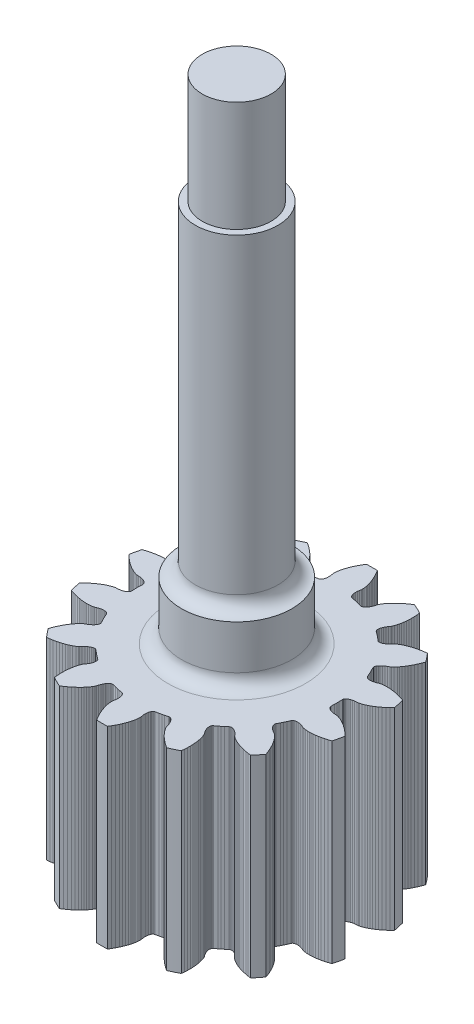
SolidWorks part; units mm, degrees
ref_plane "Front Plane" through (0, 0, 0) normal (0, 0, 1) x (1, 0, 0)
ref_plane "Top Plane" through (0, 0, 0) normal (0, 1, 0) x (1, 0, 0)
ref_plane "Right Plane" through (0, 0, 0) normal (1, 0, 0) x (0, 0, -1)
sketch "Sketch1" plane through (0, 0, 0) normal (0, 1, 0) x (1, 0, 0)
  circle A0 centre (0, 0) radius 2
  dimension "D1" = 4
extrude "Boss-Extrude1" add sketch "Sketch1" along normal blind 2.1
sketch "Sketch2" plane through (0, 2.1, 0) normal (0, 1, 0) x (1, 0, 0)
  circle A0 centre (0, 0) radius 1.5
  dimension "D1" = 3
extrude "Boss-Extrude3" add sketch "Sketch2" along normal blind 15.8
sketch "Sketch4" plane through (0, 0, 0) normal (0, -1, 0) x (1, 0, 0)
  line L0 (-3.8598, -2.7536) -> (-3.8196, -2.6568)
  line L1 (-3.8196, -2.6568) -> (-3.7768, -2.5645)
  line L2 (-3.7768, -2.5645) -> (-3.7346, -2.483)
  line L3 (-3.7346, -2.483) -> (-3.6931, -2.4103)
  line L4 (-3.6931, -2.4103) -> (-3.6512, -2.3435)
  line L5 (-3.6512, -2.3435) -> (-3.6107, -2.2846)
  line L6 (-3.6107, -2.2846) -> (-3.5723, -2.2335)
  line L7 (-3.5723, -2.2335) -> (-3.5355, -2.1885)
  line L8 (-3.5355, -2.1885) -> (-3.4731, -2.1213)
  line L9 (-3.4731, -2.1213) -> (-3.4249, -2.0772)
  line L10 (-3.4249, -2.0772) -> (-3.3949, -2.054)
  line L11 (-3.3949, -2.054) -> (-3.3412, -2.026)
  line L12 (-3.3412, -2.026) -> (-3.2813, -1.9892)
  line L13 (-3.2813, -1.9892) -> (-3.2304, -1.9514)
  line L14 (-3.2304, -1.9514) -> (-3.1885, -1.9131)
  line L15 (-3.1885, -1.9131) -> (-3.1554, -1.8752)
  line L16 (-3.1554, -1.8752) -> (-3.1311, -1.8382)
  line L17 (-3.1311, -1.8382) -> (-3.1154, -1.8029)
  line L18 (-3.1154, -1.8029) -> (-3.1082, -1.7698)
  line L19 (-3.1082, -1.7698) -> (-3.1077, -1.7543)
  line L20 (-3.1077, -1.7543) -> (-3.1092, -1.7396)
  line L21 (-3.1092, -1.7396) -> (-3.1127, -1.7258)
  line L22 (-3.1127, -1.7258) -> (-3.1181, -1.713)
  line L23 (-3.1181, -1.713) -> (-3.1739, -1.6081)
  line L24 (-3.1739, -1.6081) -> (-3.2123, -1.5307)
  line L25 (-3.2123, -1.5307) -> (-3.2488, -1.4525)
  line L26 (-3.2488, -1.4525) -> (-3.296, -1.3434)
  line L27 (-3.296, -1.3434) -> (-3.3027, -1.3312)
  line L28 (-3.3027, -1.3312) -> (-3.3113, -1.3199)
  line L29 (-3.3113, -1.3199) -> (-3.3219, -1.3096)
  line L30 (-3.3219, -1.3096) -> (-3.3343, -1.3003)
  line L31 (-3.3343, -1.3003) -> (-3.3647, -1.2854)
  line L32 (-3.3647, -1.2854) -> (-3.4021, -1.2756)
  line L33 (-3.4021, -1.2756) -> (-3.4461, -1.2715)
  line L34 (-3.4461, -1.2715) -> (-3.4964, -1.2737)
  line L35 (-3.4964, -1.2737) -> (-3.5525, -1.2827)
  line L36 (-3.5525, -1.2827) -> (-3.6138, -1.2989)
  line L37 (-3.6138, -1.2989) -> (-3.6799, -1.3228)
  line L38 (-3.6799, -1.3228) -> (-3.7353, -1.3472)
  line L39 (-3.7353, -1.3472) -> (-3.7721, -1.3563)
  line L40 (-3.7721, -1.3563) -> (-3.8366, -1.3665)
  line L41 (-3.8366, -1.3665) -> (-3.9281, -1.3733)
  line L42 (-3.9281, -1.3733) -> (-3.9862, -1.3741)
  line L43 (-3.9862, -1.3741) -> (-4.0501, -1.3722)
  line L44 (-4.0501, -1.3722) -> (-4.1213, -1.3672)
  line L45 (-4.1213, -1.3672) -> (-4.1997, -1.3583)
  line L46 (-4.1997, -1.3583) -> (-4.2825, -1.3454)
  line L47 (-4.2825, -1.3454) -> (-4.3725, -1.3275)
  line L48 (-4.3725, -1.3275) -> (-4.4713, -1.3035)
  line L49 (-4.4713, -1.3035) -> (-4.5721, -1.2745)
  line L50 (-4.5721, -1.2745) -> (-4.6753, -1.2401)
  line L51 (-4.7632, -0.8547) -> (-4.6852, -0.779)
  line L52 (-4.6852, -0.779) -> (-4.607, -0.7091)
  line L53 (-4.607, -0.7091) -> (-4.5283, -0.6446)
  line L54 (-4.5283, -0.6446) -> (-4.455, -0.5895)
  line L55 (-4.455, -0.5895) -> (-4.386, -0.542)
  line L56 (-4.386, -0.542) -> (-4.3193, -0.4999)
  line L57 (-4.3193, -0.4999) -> (-4.2573, -0.4645)
  line L58 (-4.2573, -0.4645) -> (-4.2005, -0.4351)
  line L59 (-4.2005, -0.4351) -> (-4.1478, -0.4106)
  line L60 (-4.1478, -0.4106) -> (-4.0625, -0.377)
  line L61 (-4.0625, -0.377) -> (-3.9999, -0.3582)
  line L62 (-3.9999, -0.3582) -> (-3.9628, -0.3504)
  line L63 (-3.9628, -0.3504) -> (-3.9023, -0.3484)
  line L64 (-3.9023, -0.3484) -> (-3.8324, -0.3413)
  line L65 (-3.8324, -0.3413) -> (-3.7701, -0.3293)
  line L66 (-3.7701, -0.3293) -> (-3.7157, -0.313)
  line L67 (-3.7157, -0.313) -> (-3.6694, -0.2932)
  line L68 (-3.6694, -0.2932) -> (-3.6315, -0.2704)
  line L69 (-3.6315, -0.2704) -> (-3.602, -0.2453)
  line L70 (-3.602, -0.2453) -> (-3.5812, -0.2187)
  line L71 (-3.5812, -0.2187) -> (-3.574, -0.205)
  line L72 (-3.574, -0.205) -> (-3.569, -0.1911)
  line L73 (-3.569, -0.1911) -> (-3.5661, -0.1771)
  line L74 (-3.5661, -0.1771) -> (-3.5654, -0.1632)
  line L75 (-3.5654, -0.1632) -> (-3.5702, -0.0445)
  line L76 (-3.5702, -0.0445) -> (-3.5712, 0.0419)
  line L77 (-3.5712, 0.0419) -> (-3.5702, 0.1282)
  line L78 (-3.5702, 0.1282) -> (-3.5654, 0.2469)
  line L79 (-3.5654, 0.2469) -> (-3.5661, 0.2609)
  line L80 (-3.5661, 0.2609) -> (-3.569, 0.2748)
  line L81 (-3.569, 0.2748) -> (-3.574, 0.2887)
  line L82 (-3.574, 0.2887) -> (-3.5812, 0.3024)
  line L83 (-3.5812, 0.3024) -> (-3.602, 0.329)
  line L84 (-3.602, 0.329) -> (-3.6315, 0.3541)
  line L85 (-3.6315, 0.3541) -> (-3.6694, 0.3769)
  line L86 (-3.6694, 0.3769) -> (-3.7157, 0.3967)
  line L87 (-3.7157, 0.3967) -> (-3.7701, 0.413)
  line L88 (-3.7701, 0.413) -> (-3.8324, 0.425)
  line L89 (-3.8324, 0.425) -> (-3.9023, 0.4321)
  line L90 (-3.9023, 0.4321) -> (-3.9628, 0.4341)
  line L91 (-3.9628, 0.4341) -> (-3.9999, 0.4419)
  line L92 (-3.9999, 0.4419) -> (-4.0625, 0.4607)
  line L93 (-4.0625, 0.4607) -> (-4.1478, 0.4943)
  line L94 (-4.1478, 0.4943) -> (-4.2005, 0.5188)
  line L95 (-4.2005, 0.5188) -> (-4.2573, 0.5482)
  line L96 (-4.2573, 0.5482) -> (-4.3193, 0.5837)
  line L97 (-4.3193, 0.5837) -> (-4.386, 0.6257)
  line L98 (-4.386, 0.6257) -> (-4.455, 0.6732)
  line L99 (-4.455, 0.6732) -> (-4.5283, 0.7283)
  line L100 (-4.5283, 0.7283) -> (-4.607, 0.7929)
  line L101 (-4.607, 0.7929) -> (-4.6852, 0.8627)
  line L102 (-4.6852, 0.8627) -> (-4.7632, 0.9384)
  line L103 (-4.6753, 1.3238) -> (-4.5721, 1.3582)
  line L104 (-4.5721, 1.3582) -> (-4.4713, 1.3872)
  line L105 (-4.4713, 1.3872) -> (-4.3725, 1.4112)
  line L106 (-4.3725, 1.4112) -> (-4.2825, 1.4291)
  line L107 (-4.2825, 1.4291) -> (-4.1997, 1.442)
  line L108 (-4.1997, 1.442) -> (-4.1213, 1.4509)
  line L109 (-4.1213, 1.4509) -> (-4.0501, 1.4559)
  line L110 (-4.0501, 1.4559) -> (-3.9862, 1.4578)
  line L111 (-3.9862, 1.4578) -> (-3.9281, 1.457)
  line L112 (-3.9281, 1.457) -> (-3.8366, 1.4502)
  line L113 (-3.8366, 1.4502) -> (-3.7721, 1.44)
  line L114 (-3.7721, 1.44) -> (-3.7353, 1.4309)
  line L115 (-3.7353, 1.4309) -> (-3.6799, 1.4065)
  line L116 (-3.6799, 1.4065) -> (-3.6138, 1.3826)
  line L117 (-3.6138, 1.3826) -> (-3.5525, 1.3664)
  line L118 (-3.5525, 1.3664) -> (-3.4964, 1.3574)
  line L119 (-3.4964, 1.3574) -> (-3.4461, 1.3552)
  line L120 (-3.4461, 1.3552) -> (-3.4021, 1.3593)
  line L121 (-3.4021, 1.3593) -> (-3.3647, 1.3691)
  line L122 (-3.3647, 1.3691) -> (-3.3343, 1.384)
  line L123 (-3.3343, 1.384) -> (-3.3219, 1.3933)
  line L124 (-3.3219, 1.3933) -> (-3.3113, 1.4036)
  line L125 (-3.3113, 1.4036) -> (-3.3027, 1.4149)
  line L126 (-3.3027, 1.4149) -> (-3.296, 1.4271)
  line L127 (-3.296, 1.4271) -> (-3.2488, 1.5362)
  line L128 (-3.2488, 1.5362) -> (-3.2123, 1.6144)
  line L129 (-3.2123, 1.6144) -> (-3.1739, 1.6918)
  line L130 (-3.1739, 1.6918) -> (-3.1181, 1.7967)
  line L131 (-3.1181, 1.7967) -> (-3.1127, 1.8095)
  line L132 (-3.1127, 1.8095) -> (-3.1092, 1.8233)
  line L133 (-3.1092, 1.8233) -> (-3.1077, 1.838)
  line L134 (-3.1077, 1.838) -> (-3.1082, 1.8535)
  line L135 (-3.1082, 1.8535) -> (-3.1154, 1.8866)
  line L136 (-3.1154, 1.8866) -> (-3.1311, 1.9219)
  line L137 (-3.1311, 1.9219) -> (-3.1554, 1.9589)
  line L138 (-3.1554, 1.9589) -> (-3.1885, 1.9968)
  line L139 (-3.1885, 1.9968) -> (-3.2304, 2.0351)
  line L140 (-3.2304, 2.0351) -> (-3.2813, 2.0729)
  line L141 (-3.2813, 2.0729) -> (-3.3412, 2.1097)
  line L142 (-3.3412, 2.1097) -> (-3.3949, 2.1377)
  line L143 (-3.3949, 2.1377) -> (-3.4249, 2.1609)
  line L144 (-3.4249, 2.1609) -> (-3.4731, 2.2049)
  line L145 (-3.4731, 2.2049) -> (-3.5355, 2.2722)
  line L146 (-3.5355, 2.2722) -> (-3.5723, 2.3172)
  line L147 (-3.5723, 2.3172) -> (-3.6107, 2.3683)
  line L148 (-3.6107, 2.3683) -> (-3.6512, 2.4271)
  line L149 (-3.6512, 2.4271) -> (-3.6931, 2.494)
  line L150 (-3.6931, 2.494) -> (-3.7346, 2.5667)
  line L151 (-3.7346, 2.5667) -> (-3.7768, 2.6482)
  line L152 (-3.7768, 2.6482) -> (-3.8196, 2.7405)
  line L153 (-3.8196, 2.7405) -> (-3.8598, 2.8373)
  line L154 (-3.8598, 2.8373) -> (-3.8972, 2.9394)
  line L155 (-3.6508, 3.2485) -> (-3.5429, 3.2347)
  line L156 (-3.5429, 3.2347) -> (-3.4395, 3.2171)
  line L157 (-3.4395, 3.2171) -> (-3.34, 3.1958)
  line L158 (-3.34, 3.1958) -> (-3.2512, 3.1729)
  line L159 (-3.2512, 3.1729) -> (-3.171, 3.1486)
  line L160 (-3.171, 3.1486) -> (-3.0966, 3.1226)
  line L161 (-3.0966, 3.1226) -> (-3.0302, 3.0963)
  line L162 (-3.0302, 3.0963) -> (-2.9718, 3.0702)
  line L163 (-2.9718, 3.0702) -> (-2.9198, 3.0443)
  line L164 (-2.9198, 3.0443) -> (-2.8403, 2.9985)
  line L165 (-2.8403, 2.9985) -> (-2.7866, 2.9613)
  line L166 (-2.7866, 2.9613) -> (-2.7574, 2.9372)
  line L167 (-2.7574, 2.9372) -> (-2.7181, 2.8911)
  line L168 (-2.7181, 2.8911) -> (-2.6689, 2.8409)
  line L169 (-2.6689, 2.8409) -> (-2.6207, 2.7996)
  line L170 (-2.6207, 2.7996) -> (-2.5741, 2.7672)
  line L171 (-2.5741, 2.7672) -> (-2.5297, 2.7435)
  line L172 (-2.5297, 2.7435) -> (-2.4883, 2.728)
  line L173 (-2.4883, 2.728) -> (-2.4503, 2.7206)
  line L174 (-2.4503, 2.7206) -> (-2.4165, 2.7209)
  line L175 (-2.4165, 2.7209) -> (-2.4013, 2.7238)
  line L176 (-2.4013, 2.7238) -> (-2.3873, 2.7285)
  line L177 (-2.3873, 2.7285) -> (-2.3746, 2.735)
  line L178 (-2.3746, 2.735) -> (-2.3633, 2.7431)
  line L179 (-2.3633, 2.7431) -> (-2.2734, 2.8209)
  line L180 (-2.2734, 2.8209) -> (-2.2066, 2.8755)
  line L181 (-2.2066, 2.8755) -> (-2.1384, 2.9286)
  line L182 (-2.1384, 2.9286) -> (-2.0426, 2.9989)
  line L183 (-2.0426, 2.9989) -> (-2.0322, 3.0081)
  line L184 (-2.0322, 3.0081) -> (-2.023, 3.019)
  line L185 (-2.023, 3.019) -> (-2.0153, 3.0316)
  line L186 (-2.0153, 3.0316) -> (-2.0091, 3.0458)
  line L187 (-2.0091, 3.0458) -> (-2.0013, 3.0787)
  line L188 (-2.0013, 3.0787) -> (-2, 3.1174)
  line L189 (-2, 3.1174) -> (-2.0059, 3.1612)
  line L190 (-2.0059, 3.1612) -> (-2.0192, 3.2098)
  line L191 (-2.0192, 3.2098) -> (-2.0404, 3.2624)
  line L192 (-2.0404, 3.2624) -> (-2.0699, 3.3186)
  line L193 (-2.0699, 3.3186) -> (-2.1079, 3.3777)
  line L194 (-2.1079, 3.3777) -> (-2.1441, 3.4263)
  line L195 (-2.1441, 3.4263) -> (-2.1611, 3.4601)
  line L196 (-2.1611, 3.4601) -> (-2.1854, 3.5208)
  line L197 (-2.1854, 3.5208) -> (-2.2124, 3.6084)
  line L198 (-2.2124, 3.6084) -> (-2.2261, 3.665)
  line L199 (-2.2261, 3.665) -> (-2.2385, 3.7277)
  line L200 (-2.2385, 3.7277) -> (-2.2494, 3.7982)
  line L201 (-2.2494, 3.7982) -> (-2.2582, 3.8766)
  line L202 (-2.2582, 3.8766) -> (-2.264, 3.9602)
  line L203 (-2.264, 3.9602) -> (-2.2666, 4.0519)
  line L204 (-2.2666, 4.0519) -> (-2.2652, 4.1536)
  line L205 (-2.2652, 4.1536) -> (-2.2594, 4.2583)
  line L206 (-2.2594, 4.2583) -> (-2.2488, 4.3665)
  line L207 (-1.8926, 4.538) -> (-1.8014, 4.4788)
  line L208 (-1.8014, 4.4788) -> (-1.7159, 4.4181)
  line L209 (-1.7159, 4.4181) -> (-1.6355, 4.3558)
  line L210 (-1.6355, 4.3558) -> (-1.5655, 4.2966)
  line L211 (-1.5655, 4.2966) -> (-1.5038, 4.2399)
  line L212 (-1.5038, 4.2399) -> (-1.448, 4.1842)
  line L213 (-1.448, 4.1842) -> (-1.3996, 4.1316)
  line L214 (-1.3996, 4.1316) -> (-1.3583, 4.0828)
  line L215 (-1.3583, 4.0828) -> (-1.3227, 4.0369)
  line L216 (-1.3227, 4.0369) -> (-1.271, 3.9611)
  line L217 (-1.271, 3.9611) -> (-1.2387, 3.9043)
  line L218 (-1.2387, 3.9043) -> (-1.2228, 3.8699)
  line L219 (-1.2228, 3.8699) -> (-1.2074, 3.8113)
  line L220 (-1.2074, 3.8113) -> (-1.1849, 3.7448)
  line L221 (-1.1849, 3.7448) -> (-1.1593, 3.6867)
  line L222 (-1.1593, 3.6867) -> (-1.1314, 3.6373)
  line L223 (-1.1314, 3.6373) -> (-1.1018, 3.5966)
  line L224 (-1.1018, 3.5966) -> (-1.0711, 3.5647)
  line L225 (-1.0711, 3.5647) -> (-1.0401, 3.5416)
  line L226 (-1.0401, 3.5416) -> (-1.0095, 3.5271)
  line L227 (-1.0095, 3.5271) -> (-0.9945, 3.5232)
  line L228 (-0.9945, 3.5232) -> (-0.9799, 3.5214)
  line L229 (-0.9799, 3.5214) -> (-0.9657, 3.5217)
  line L230 (-0.9657, 3.5217) -> (-0.952, 3.5241)
  line L231 (-0.952, 3.5241) -> (-0.8372, 3.5552)
  line L232 (-0.8372, 3.5552) -> (-0.7533, 3.5754)
  line L233 (-0.7533, 3.5754) -> (-0.6689, 3.5936)
  line L234 (-0.6689, 3.5936) -> (-0.5521, 3.6154)
  line L235 (-0.5521, 3.6154) -> (-0.5386, 3.6192)
  line L236 (-0.5386, 3.6192) -> (-0.5257, 3.625)
  line L237 (-0.5257, 3.625) -> (-0.5133, 3.633)
  line L238 (-0.5133, 3.633) -> (-0.5015, 3.6431)
  line L239 (-0.5015, 3.6431) -> (-0.4802, 3.6694)
  line L240 (-0.4802, 3.6694) -> (-0.4623, 3.7037)
  line L241 (-0.4623, 3.7037) -> (-0.4485, 3.7457)
  line L242 (-0.4485, 3.7457) -> (-0.4395, 3.7952)
  line L243 (-0.4395, 3.7952) -> (-0.4357, 3.8519)
  line L244 (-0.4357, 3.8519) -> (-0.4379, 3.9153)
  line L245 (-0.4379, 3.9153) -> (-0.4465, 3.985)
  line L246 (-0.4465, 3.985) -> (-0.458, 4.0445)
  line L247 (-0.458, 4.0445) -> (-0.4587, 4.0824)
  line L248 (-0.4587, 4.0824) -> (-0.4543, 4.1475)
  line L249 (-0.4543, 4.1475) -> (-0.4405, 4.2382)
  line L250 (-0.4405, 4.2382) -> (-0.4283, 4.2951)
  line L251 (-0.4283, 4.2951) -> (-0.4123, 4.357)
  line L252 (-0.4123, 4.357) -> (-0.3915, 4.4253)
  line L253 (-0.3915, 4.4253) -> (-0.3654, 4.4997)
  line L254 (-0.3654, 4.4997) -> (-0.3344, 4.5775)
  line L255 (-0.3344, 4.5775) -> (-0.297, 4.6613)
  line L256 (-0.297, 4.6613) -> (-0.2516, 4.7523)
  line L257 (-0.2516, 4.7523) -> (-0.2009, 4.8441)
  line L258 (-0.2009, 4.8441) -> (-0.1444, 4.9371)
  line L259 (0.2509, 4.9371) -> (0.3073, 4.8441)
  line L260 (0.3073, 4.8441) -> (0.358, 4.7523)
  line L261 (0.358, 4.7523) -> (0.4034, 4.6613)
  line L262 (0.4034, 4.6613) -> (0.4409, 4.5775)
  line L263 (0.4409, 4.5775) -> (0.4719, 4.4997)
  line L264 (0.4719, 4.4997) -> (0.498, 4.4253)
  line L265 (0.498, 4.4253) -> (0.5187, 4.357)
  line L266 (0.5187, 4.357) -> (0.5348, 4.2951)
  line L267 (0.5348, 4.2951) -> (0.547, 4.2382)
  line L268 (0.547, 4.2382) -> (0.5607, 4.1475)
  line L269 (0.5607, 4.1475) -> (0.5651, 4.0824)
  line L270 (0.5651, 4.0824) -> (0.5645, 4.0445)
  line L271 (0.5645, 4.0445) -> (0.5529, 3.985)
  line L272 (0.5529, 3.985) -> (0.5443, 3.9153)
  line L273 (0.5443, 3.9153) -> (0.5422, 3.8519)
  line L274 (0.5422, 3.8519) -> (0.5459, 3.7952)
  line L275 (0.5459, 3.7952) -> (0.555, 3.7457)
  line L276 (0.555, 3.7457) -> (0.5687, 3.7037)
  line L277 (0.5687, 3.7037) -> (0.5866, 3.6694)
  line L278 (0.5866, 3.6694) -> (0.6079, 3.6431)
  line L279 (0.6079, 3.6431) -> (0.6197, 3.633)
  line L280 (0.6197, 3.633) -> (0.6321, 3.625)
  line L281 (0.6321, 3.625) -> (0.6451, 3.6192)
  line L282 (0.6451, 3.6192) -> (0.6585, 3.6154)
  line L283 (0.6585, 3.6154) -> (0.7753, 3.5936)
  line L284 (0.7753, 3.5936) -> (0.8597, 3.5754)
  line L285 (0.8597, 3.5754) -> (0.9437, 3.5552)
  line L286 (0.9437, 3.5552) -> (1.0584, 3.5241)
  line L287 (1.0584, 3.5241) -> (1.0721, 3.5217)
  line L288 (1.0721, 3.5217) -> (1.0863, 3.5214)
  line L289 (1.0863, 3.5214) -> (1.101, 3.5232)
  line L290 (1.101, 3.5232) -> (1.1159, 3.5271)
  line L291 (1.1159, 3.5271) -> (1.1466, 3.5416)
  line L292 (1.1466, 3.5416) -> (1.1776, 3.5647)
  line L293 (1.1776, 3.5647) -> (1.2082, 3.5966)
  line L294 (1.2082, 3.5966) -> (1.2378, 3.6373)
  line L295 (1.2378, 3.6373) -> (1.2658, 3.6867)
  line L296 (1.2658, 3.6867) -> (1.2914, 3.7448)
  line L297 (1.2914, 3.7448) -> (1.3139, 3.8113)
  line L298 (1.3139, 3.8113) -> (1.3293, 3.8699)
  line L299 (1.3293, 3.8699) -> (1.3451, 3.9043)
  line L300 (1.3451, 3.9043) -> (1.3774, 3.9611)
  line L301 (1.3774, 3.9611) -> (1.4291, 4.0369)
  line L302 (1.4291, 4.0369) -> (1.4648, 4.0828)
  line L303 (1.4648, 4.0828) -> (1.5061, 4.1316)
  line L304 (1.5061, 4.1316) -> (1.5544, 4.1842)
  line L305 (1.5544, 4.1842) -> (1.6102, 4.2399)
  line L306 (1.6102, 4.2399) -> (1.6719, 4.2966)
  line L307 (1.6719, 4.2966) -> (1.742, 4.3558)
  line L308 (1.742, 4.3558) -> (1.8224, 4.4181)
  line L309 (1.8224, 4.4181) -> (1.9079, 4.4788)
  line L310 (1.9079, 4.4788) -> (1.9991, 4.538)
  line L311 (2.3553, 4.3665) -> (2.3658, 4.2583)
  line L312 (2.3658, 4.2583) -> (2.3717, 4.1536)
  line L313 (2.3717, 4.1536) -> (2.3731, 4.0519)
  line L314 (2.3731, 4.0519) -> (2.3705, 3.9601)
  line L315 (2.3705, 3.9601) -> (2.3646, 3.8766)
  line L316 (2.3646, 3.8766) -> (2.3558, 3.7982)
  line L317 (2.3558, 3.7982) -> (2.3449, 3.7277)
  line L318 (2.3449, 3.7277) -> (2.3325, 3.6649)
  line L319 (2.3325, 3.6649) -> (2.3188, 3.6084)
  line L320 (2.3188, 3.6084) -> (2.2918, 3.5208)
  line L321 (2.2918, 3.5208) -> (2.2675, 3.4601)
  line L322 (2.2675, 3.4601) -> (2.2505, 3.4263)
  line L323 (2.2505, 3.4263) -> (2.2143, 3.3777)
  line L324 (2.2143, 3.3777) -> (2.1763, 3.3186)
  line L325 (2.1763, 3.3186) -> (2.1469, 3.2624)
  line L326 (2.1469, 3.2624) -> (2.1257, 3.2098)
  line L327 (2.1257, 3.2098) -> (2.1123, 3.1612)
  line L328 (2.1123, 3.1612) -> (2.1065, 3.1174)
  line L329 (2.1065, 3.1174) -> (2.1077, 3.0787)
  line L330 (2.1077, 3.0787) -> (2.1155, 3.0458)
  line L331 (2.1155, 3.0458) -> (2.1218, 3.0316)
  line L332 (2.1218, 3.0316) -> (2.1295, 3.019)
  line L333 (2.1295, 3.019) -> (2.1386, 3.0081)
  line L334 (2.1386, 3.0081) -> (2.1491, 2.9989)
  line L335 (2.1491, 2.9989) -> (2.2449, 2.9286)
  line L336 (2.2449, 2.9286) -> (2.313, 2.8755)
  line L337 (2.313, 2.8755) -> (2.3799, 2.8209)
  line L338 (2.3799, 2.8209) -> (2.4698, 2.7431)
  line L339 (2.4698, 2.7431) -> (2.4811, 2.735)
  line L340 (2.4811, 2.735) -> (2.4937, 2.7285)
  line L341 (2.4937, 2.7285) -> (2.5077, 2.7238)
  line L342 (2.5077, 2.7238) -> (2.5229, 2.7209)
  line L343 (2.5229, 2.7209) -> (2.5568, 2.7206)
  line L344 (2.5568, 2.7206) -> (2.5947, 2.728)
  line L345 (2.5947, 2.728) -> (2.6362, 2.7434)
  line L346 (2.6362, 2.7434) -> (2.6805, 2.7672)
  line L347 (2.6805, 2.7672) -> (2.7272, 2.7996)
  line L348 (2.7272, 2.7996) -> (2.7754, 2.8408)
  line L349 (2.7754, 2.8408) -> (2.8245, 2.8911)
  line L350 (2.8245, 2.8911) -> (2.8638, 2.9371)
  line L351 (2.8638, 2.9371) -> (2.8931, 2.9613)
  line L352 (2.8931, 2.9613) -> (2.9468, 2.9985)
  line L353 (2.9468, 2.9985) -> (3.0262, 3.0443)
  line L354 (3.0262, 3.0443) -> (3.0783, 3.0702)
  line L355 (3.0783, 3.0702) -> (3.1367, 3.0963)
  line L356 (3.1367, 3.0963) -> (3.203, 3.1226)
  line L357 (3.203, 3.1226) -> (3.2775, 3.1486)
  line L358 (3.2775, 3.1486) -> (3.3577, 3.1729)
  line L359 (3.3577, 3.1729) -> (3.4465, 3.1958)
  line L360 (3.4465, 3.1958) -> (3.546, 3.2171)
  line L361 (3.546, 3.2171) -> (3.6494, 3.2347)
  line L362 (3.6494, 3.2347) -> (3.7572, 3.2485)
  line L363 (4.0037, 2.9394) -> (3.9662, 2.8373)
  line L364 (3.9662, 2.8373) -> (3.9261, 2.7405)
  line L365 (3.9261, 2.7405) -> (3.8832, 2.6482)
  line L366 (3.8832, 2.6482) -> (3.8411, 2.5667)
  line L367 (3.8411, 2.5667) -> (3.7995, 2.494)
  line L368 (3.7995, 2.494) -> (3.7576, 2.4271)
  line L369 (3.7576, 2.4271) -> (3.7172, 2.3683)
  line L370 (3.7172, 2.3683) -> (3.6788, 2.3172)
  line L371 (3.6788, 2.3172) -> (3.6419, 2.2722)
  line L372 (3.6419, 2.2722) -> (3.5796, 2.2049)
  line L373 (3.5796, 2.2049) -> (3.5314, 2.1609)
  line L374 (3.5314, 2.1609) -> (3.5014, 2.1377)
  line L375 (3.5014, 2.1377) -> (3.4477, 2.1097)
  line L376 (3.4477, 2.1097) -> (3.3878, 2.0729)
  line L377 (3.3878, 2.0729) -> (3.3369, 2.0351)
  line L378 (3.3369, 2.0351) -> (3.2949, 1.9968)
  line L379 (3.2949, 1.9968) -> (3.2618, 1.9589)
  line L380 (3.2618, 1.9589) -> (3.2376, 1.9219)
  line L381 (3.2376, 1.9219) -> (3.2219, 1.8866)
  line L382 (3.2219, 1.8866) -> (3.2147, 1.8535)
  line L383 (3.2147, 1.8535) -> (3.2141, 1.838)
  line L384 (3.2141, 1.838) -> (3.2156, 1.8233)
  line L385 (3.2156, 1.8233) -> (3.2191, 1.8095)
  line L386 (3.2191, 1.8095) -> (3.2245, 1.7967)
  line L387 (3.2245, 1.7967) -> (3.2803, 1.6918)
  line L388 (3.2803, 1.6918) -> (3.3187, 1.6144)
  line L389 (3.3187, 1.6144) -> (3.3552, 1.5362)
  line L390 (3.3552, 1.5362) -> (3.4025, 1.4271)
  line L391 (3.4025, 1.4271) -> (3.4091, 1.4149)
  line L392 (3.4091, 1.4149) -> (3.4178, 1.4036)
  line L393 (3.4178, 1.4036) -> (3.4283, 1.3933)
  line L394 (3.4283, 1.3933) -> (3.4407, 1.384)
  line L395 (3.4407, 1.384) -> (3.4711, 1.3691)
  line L396 (3.4711, 1.3691) -> (3.5085, 1.3593)
  line L397 (3.5085, 1.3593) -> (3.5526, 1.3552)
  line L398 (3.5526, 1.3552) -> (3.6029, 1.3574)
  line L399 (3.6029, 1.3574) -> (3.6589, 1.3664)
  line L400 (3.6589, 1.3664) -> (3.7202, 1.3826)
  line L401 (3.7202, 1.3826) -> (3.7863, 1.4065)
  line L402 (3.7863, 1.4065) -> (3.8417, 1.4309)
  line L403 (3.8417, 1.4309) -> (3.8785, 1.44)
  line L404 (3.8785, 1.44) -> (3.9431, 1.4502)
  line L405 (3.9431, 1.4502) -> (4.0345, 1.457)
  line L406 (4.0345, 1.457) -> (4.0927, 1.4578)
  line L407 (4.0927, 1.4578) -> (4.1566, 1.4559)
  line L408 (4.1566, 1.4559) -> (4.2278, 1.4509)
  line L409 (4.2278, 1.4509) -> (4.3061, 1.442)
  line L410 (4.3061, 1.442) -> (4.3889, 1.4291)
  line L411 (4.3889, 1.4291) -> (4.4789, 1.4112)
  line L412 (4.4789, 1.4112) -> (4.5778, 1.3872)
  line L413 (4.5778, 1.3872) -> (4.6786, 1.3582)
  line L414 (4.6786, 1.3582) -> (4.7817, 1.3238)
  line L415 (4.8697, 0.9384) -> (4.7917, 0.8627)
  line L416 (4.7917, 0.8627) -> (4.7134, 0.7928)
  line L417 (4.7134, 0.7928) -> (4.6348, 0.7283)
  line L418 (4.6348, 0.7283) -> (4.5614, 0.6732)
  line L419 (4.5614, 0.6732) -> (4.4925, 0.6257)
  line L840 (4.4925, 0.6257) -> (4.4257, 0.5836)
  line L841 (4.4257, 0.5836) -> (4.3638, 0.5482)
  line L842 (4.3638, 0.5482) -> (4.307, 0.5188)
  line L843 (4.307, 0.5188) -> (4.2543, 0.4943)
  line L844 (4.2543, 0.4943) -> (4.1689, 0.4607)
  line L845 (4.1689, 0.4607) -> (4.1063, 0.4419)
  line L846 (4.1063, 0.4419) -> (4.0693, 0.4341)
  line L847 (4.0693, 0.4341) -> (4.0087, 0.4321)
  line L848 (4.0087, 0.4321) -> (3.9388, 0.425)
  line L849 (3.9388, 0.425) -> (3.8765, 0.413)
  line L850 (3.8765, 0.413) -> (3.8221, 0.3967)
  line L851 (3.8221, 0.3967) -> (3.7759, 0.3769)
  line L852 (3.7759, 0.3769) -> (3.7379, 0.3541)
  line L853 (3.7379, 0.3541) -> (3.7085, 0.329)
  line L854 (3.7085, 0.329) -> (3.6876, 0.3024)
  line L855 (3.6876, 0.3024) -> (3.6804, 0.2887)
  line L856 (3.6804, 0.2887) -> (3.6754, 0.2748)
  line L857 (3.6754, 0.2748) -> (3.6725, 0.2608)
  line L858 (3.6725, 0.2608) -> (3.6719, 0.2469)
  line L859 (3.6719, 0.2469) -> (3.6766, 0.1282)
  line L860 (3.6766, 0.1282) -> (3.6776, 0.0418)
  line L861 (3.6776, 0.0418) -> (3.6766, -0.0445)
  line L862 (3.6766, -0.0445) -> (3.6719, -0.1632)
  line L863 (3.6719, -0.1632) -> (3.6725, -0.1772)
  line L864 (3.6725, -0.1772) -> (3.6754, -0.1911)
  line L865 (3.6754, -0.1911) -> (3.6804, -0.205)
  line L866 (3.6804, -0.205) -> (3.6876, -0.2187)
  line L867 (3.6876, -0.2187) -> (3.7085, -0.2453)
  line L868 (3.7085, -0.2453) -> (3.7379, -0.2704)
  line L869 (3.7379, -0.2704) -> (3.7759, -0.2932)
  line L870 (3.7759, -0.2932) -> (3.8221, -0.313)
  line L871 (3.8221, -0.313) -> (3.8765, -0.3293)
  line L872 (3.8765, -0.3293) -> (3.9388, -0.3413)
  line L873 (3.9388, -0.3413) -> (4.0087, -0.3484)
  line L874 (4.0087, -0.3484) -> (4.0693, -0.3504)
  line L875 (4.0693, -0.3504) -> (4.1063, -0.3582)
  line L876 (4.1063, -0.3582) -> (4.1689, -0.377)
  line L877 (4.1689, -0.377) -> (4.2543, -0.4106)
  line L878 (4.2543, -0.4106) -> (4.307, -0.4351)
  line L879 (4.307, -0.4351) -> (4.3638, -0.4645)
  line L880 (4.3638, -0.4645) -> (4.4257, -0.5)
  line L881 (4.4257, -0.5) -> (4.4925, -0.542)
  line L882 (4.4925, -0.542) -> (4.5614, -0.5895)
  line L883 (4.5614, -0.5895) -> (4.6348, -0.6446)
  line L884 (4.6348, -0.6446) -> (4.7134, -0.7092)
  line L885 (4.7134, -0.7092) -> (4.7917, -0.779)
  line L886 (4.7917, -0.779) -> (4.8697, -0.8547)
  line L887 (4.7817, -1.2401) -> (4.6786, -1.2745)
  line L888 (4.6786, -1.2745) -> (4.5778, -1.3035)
  line L889 (4.5778, -1.3035) -> (4.4789, -1.3275)
  line L890 (4.4789, -1.3275) -> (4.3889, -1.3454)
  line L891 (4.3889, -1.3454) -> (4.3061, -1.3583)
  line L892 (4.3061, -1.3583) -> (4.2278, -1.3672)
  line L893 (4.2278, -1.3672) -> (4.1566, -1.3722)
  line L894 (4.1566, -1.3722) -> (4.0927, -1.3741)
  line L895 (4.0927, -1.3741) -> (4.0345, -1.3733)
  line L896 (4.0345, -1.3733) -> (3.9431, -1.3665)
  line L897 (3.9431, -1.3665) -> (3.8785, -1.3563)
  line L898 (3.8785, -1.3563) -> (3.8417, -1.3472)
  line L899 (3.8417, -1.3472) -> (3.7863, -1.3228)
  line L900 (3.7863, -1.3228) -> (3.7202, -1.2989)
  line L901 (3.7202, -1.2989) -> (3.6589, -1.2827)
  line L902 (3.6589, -1.2827) -> (3.6029, -1.2737)
  line L903 (3.6029, -1.2737) -> (3.5526, -1.2715)
  line L904 (3.5526, -1.2715) -> (3.5085, -1.2756)
  line L905 (3.5085, -1.2756) -> (3.4711, -1.2854)
  line L906 (3.4711, -1.2854) -> (3.4407, -1.3003)
  line L907 (3.4407, -1.3003) -> (3.4283, -1.3096)
  line L908 (3.4283, -1.3096) -> (3.4178, -1.3199)
  line L909 (3.4178, -1.3199) -> (3.4091, -1.3312)
  line L910 (3.4091, -1.3312) -> (3.4025, -1.3434)
  line L911 (3.4025, -1.3434) -> (3.3552, -1.4525)
  line L912 (3.3552, -1.4525) -> (3.3187, -1.5307)
  line L913 (3.3187, -1.5307) -> (3.2803, -1.6081)
  line L914 (3.2803, -1.6081) -> (3.2245, -1.713)
  line L915 (3.2245, -1.713) -> (3.2191, -1.7258)
  line L916 (3.2191, -1.7258) -> (3.2156, -1.7396)
  line L917 (3.2156, -1.7396) -> (3.2141, -1.7543)
  line L918 (3.2141, -1.7543) -> (3.2147, -1.7698)
  line L919 (3.2147, -1.7698) -> (3.2219, -1.8029)
  line L920 (3.2219, -1.8029) -> (3.2376, -1.8382)
  line L921 (3.2376, -1.8382) -> (3.2619, -1.8752)
  line L922 (3.2619, -1.8752) -> (3.2949, -1.9132)
  line L923 (3.2949, -1.9132) -> (3.3369, -1.9514)
  line L924 (3.3369, -1.9514) -> (3.3878, -1.9892)
  line L925 (3.3878, -1.9892) -> (3.4477, -2.026)
  line L926 (3.4477, -2.026) -> (3.5014, -2.054)
  line L927 (3.5014, -2.054) -> (3.5314, -2.0772)
  line L928 (3.5314, -2.0772) -> (3.5796, -2.1213)
  line L929 (3.5796, -2.1213) -> (3.6419, -2.1885)
  line L930 (3.6419, -2.1885) -> (3.6788, -2.2335)
  line L931 (3.6788, -2.2335) -> (3.7172, -2.2846)
  line L932 (3.7172, -2.2846) -> (3.7576, -2.3435)
  line L933 (3.7576, -2.3435) -> (3.7995, -2.4103)
  line L934 (3.7995, -2.4103) -> (3.8411, -2.483)
  line L935 (3.8411, -2.483) -> (3.8832, -2.5645)
  line L936 (3.8832, -2.5645) -> (3.9261, -2.6568)
  line L937 (3.9261, -2.6568) -> (3.9662, -2.7536)
  line L938 (3.9662, -2.7536) -> (4.0037, -2.8557)
  line L939 (3.7572, -3.1648) -> (3.6493, -3.151)
  line L940 (3.6493, -3.151) -> (3.546, -3.1334)
  line L941 (3.546, -3.1334) -> (3.4465, -3.1121)
  line L942 (3.4465, -3.1121) -> (3.3576, -3.0892)
  line L943 (3.3576, -3.0892) -> (3.2775, -3.0649)
  line L944 (3.2775, -3.0649) -> (3.203, -3.0389)
  line L945 (3.203, -3.0389) -> (3.1367, -3.0126)
  line L946 (3.1367, -3.0126) -> (3.0783, -2.9865)
  line L947 (3.0783, -2.9865) -> (3.0262, -2.9606)
  line L948 (3.0262, -2.9606) -> (2.9468, -2.9148)
  line L949 (2.9468, -2.9148) -> (2.8931, -2.8776)
  line L950 (2.8931, -2.8776) -> (2.8638, -2.8535)
  line L951 (2.8638, -2.8535) -> (2.8245, -2.8074)
  line L952 (2.8245, -2.8074) -> (2.7754, -2.7572)
  line L953 (2.7754, -2.7572) -> (2.7272, -2.716)
  line L954 (2.7272, -2.716) -> (2.6805, -2.6836)
  line L955 (2.6805, -2.6836) -> (2.6362, -2.6598)
  line L956 (2.6362, -2.6598) -> (2.5947, -2.6443)
  line L957 (2.5947, -2.6443) -> (2.5568, -2.6369)
  line L958 (2.5568, -2.6369) -> (2.5229, -2.6372)
  line L959 (2.5229, -2.6372) -> (2.5077, -2.6401)
  line L960 (2.5077, -2.6401) -> (2.4937, -2.6449)
  line L961 (2.4937, -2.6449) -> (2.481, -2.6513)
  line L962 (2.481, -2.6513) -> (2.4698, -2.6595)
  line L963 (2.4698, -2.6595) -> (2.3799, -2.7372)
  line L964 (2.3799, -2.7372) -> (2.313, -2.7918)
  line L965 (2.313, -2.7918) -> (2.2449, -2.8449)
  line L966 (2.2449, -2.8449) -> (2.1491, -2.9152)
  line L967 (2.1491, -2.9152) -> (2.1386, -2.9244)
  line L968 (2.1386, -2.9244) -> (2.1295, -2.9353)
  line L969 (2.1295, -2.9353) -> (2.1218, -2.9479)
  line L970 (2.1218, -2.9479) -> (2.1155, -2.9621)
  line L971 (2.1155, -2.9621) -> (2.1077, -2.995)
  line L972 (2.1077, -2.995) -> (2.1065, -3.0337)
  line L973 (2.1065, -3.0337) -> (2.1123, -3.0775)
  line L974 (2.1123, -3.0775) -> (2.1256, -3.1261)
  line L975 (2.1256, -3.1261) -> (2.1469, -3.1787)
  line L976 (2.1469, -3.1787) -> (2.1763, -3.2349)
  line L977 (2.1763, -3.2349) -> (2.2143, -3.294)
  line L978 (2.2143, -3.294) -> (2.2505, -3.3426)
  line L979 (2.2505, -3.3426) -> (2.2675, -3.3765)
  line L980 (2.2675, -3.3765) -> (2.2918, -3.4371)
  line L981 (2.2918, -3.4371) -> (2.3188, -3.5247)
  line L982 (2.3188, -3.5247) -> (2.3325, -3.5813)
  line L983 (2.3325, -3.5813) -> (2.3449, -3.644)
  line L984 (2.3449, -3.644) -> (2.3558, -3.7145)
  line L985 (2.3558, -3.7145) -> (2.3646, -3.7929)
  line L986 (2.3646, -3.7929) -> (2.3704, -3.8765)
  line L987 (2.3704, -3.8765) -> (2.3731, -3.9682)
  line L988 (2.3731, -3.9682) -> (2.3717, -4.0699)
  line L989 (2.3717, -4.0699) -> (2.3658, -4.1746)
  line L990 (2.3658, -4.1746) -> (2.3553, -4.2828)
  line L991 (1.9991, -4.4543) -> (1.9079, -4.3951)
  line L992 (1.9079, -4.3951) -> (1.8224, -4.3344)
  line L993 (1.8224, -4.3344) -> (1.742, -4.2721)
  line L994 (1.742, -4.2721) -> (1.6719, -4.2129)
  line L995 (1.6719, -4.2129) -> (1.6102, -4.1562)
  line L996 (1.6102, -4.1562) -> (1.5544, -4.1005)
  line L997 (1.5544, -4.1005) -> (1.5061, -4.0479)
  line L998 (1.5061, -4.0479) -> (1.4648, -3.9991)
  line L999 (1.4648, -3.9991) -> (1.4291, -3.9532)
  line L1000 (1.4291, -3.9532) -> (1.3774, -3.8774)
  line L1001 (1.3774, -3.8774) -> (1.3452, -3.8206)
  line L1002 (1.3452, -3.8206) -> (1.3293, -3.7862)
  line L1003 (1.3293, -3.7862) -> (1.3139, -3.7276)
  line L1004 (1.3139, -3.7276) -> (1.2914, -3.6611)
  line L1005 (1.2914, -3.6611) -> (1.2658, -3.603)
  line L1006 (1.2658, -3.603) -> (1.2379, -3.5536)
  line L1007 (1.2379, -3.5536) -> (1.2082, -3.5129)
  line L1008 (1.2082, -3.5129) -> (1.1776, -3.481)
  line L1009 (1.1776, -3.481) -> (1.1466, -3.4579)
  line L1010 (1.1466, -3.4579) -> (1.1159, -3.4435)
  line L1011 (1.1159, -3.4435) -> (1.101, -3.4395)
  line L1012 (1.101, -3.4395) -> (1.0863, -3.4377)
  line L1013 (1.0863, -3.4377) -> (1.0721, -3.438)
  line L1014 (1.0721, -3.438) -> (1.0584, -3.4404)
  line L1015 (1.0584, -3.4404) -> (0.9437, -3.4715)
  line L1016 (0.9437, -3.4715) -> (0.8597, -3.4917)
  line L1017 (0.8597, -3.4917) -> (0.7753, -3.5099)
  line L1018 (0.7753, -3.5099) -> (0.6585, -3.5317)
  line L1019 (0.6585, -3.5317) -> (0.6451, -3.5355)
  line L1020 (0.6451, -3.5355) -> (0.6321, -3.5413)
  line L1021 (0.6321, -3.5413) -> (0.6197, -3.5493)
  line L1022 (0.6197, -3.5493) -> (0.608, -3.5594)
  line L1023 (0.608, -3.5594) -> (0.5866, -3.5857)
  line L1024 (0.5866, -3.5857) -> (0.5687, -3.62)
  line L1025 (0.5687, -3.62) -> (0.555, -3.662)
  line L1026 (0.555, -3.662) -> (0.5459, -3.7115)
  line L1027 (0.5459, -3.7115) -> (0.5422, -3.7682)
  line L1028 (0.5422, -3.7682) -> (0.5443, -3.8316)
  line L1029 (0.5443, -3.8316) -> (0.5529, -3.9013)
  line L1030 (0.5529, -3.9013) -> (0.5645, -3.9608)
  line L1031 (0.5645, -3.9608) -> (0.5651, -3.9987)
  line L1032 (0.5651, -3.9987) -> (0.5607, -4.0639)
  line L1033 (0.5607, -4.0639) -> (0.547, -4.1545)
  line L1034 (0.547, -4.1545) -> (0.5348, -4.2114)
  line L1035 (0.5348, -4.2114) -> (0.5187, -4.2733)
  line L1036 (0.5187, -4.2733) -> (0.498, -4.3416)
  line L1037 (0.498, -4.3416) -> (0.4719, -4.416)
  line L1038 (0.4719, -4.416) -> (0.4409, -4.4938)
  line L1039 (0.4409, -4.4938) -> (0.4034, -4.5776)
  line L1040 (0.4034, -4.5776) -> (0.358, -4.6686)
  line L1041 (0.358, -4.6686) -> (0.3074, -4.7604)
  line L1042 (0.3074, -4.7604) -> (0.2509, -4.8534)
  line L1043 (-0.1444, -4.8534) -> (-0.2009, -4.7604)
  line L1044 (-0.2009, -4.7604) -> (-0.2516, -4.6686)
  line L1045 (-0.2516, -4.6686) -> (-0.297, -4.5776)
  line L1046 (-0.297, -4.5776) -> (-0.3344, -4.4938)
  line L1047 (-0.3344, -4.4938) -> (-0.3654, -4.416)
  line L1048 (-0.3654, -4.416) -> (-0.3915, -4.3416)
  line L1049 (-0.3915, -4.3416) -> (-0.4123, -4.2733)
  line L1050 (-0.4123, -4.2733) -> (-0.4283, -4.2114)
  line L1051 (-0.4283, -4.2114) -> (-0.4405, -4.1545)
  line L1052 (-0.4405, -4.1545) -> (-0.4543, -4.0638)
  line L1053 (-0.4543, -4.0638) -> (-0.4587, -3.9987)
  line L1054 (-0.4587, -3.9987) -> (-0.458, -3.9608)
  line L1055 (-0.458, -3.9608) -> (-0.4465, -3.9013)
  line L1056 (-0.4465, -3.9013) -> (-0.4379, -3.8316)
  line L1057 (-0.4379, -3.8316) -> (-0.4357, -3.7682)
  line L1058 (-0.4357, -3.7682) -> (-0.4395, -3.7115)
  line L1059 (-0.4395, -3.7115) -> (-0.4485, -3.662)
  line L1060 (-0.4485, -3.662) -> (-0.4623, -3.62)
  line L1061 (-0.4623, -3.62) -> (-0.4802, -3.5857)
  line L1062 (-0.4802, -3.5857) -> (-0.5015, -3.5594)
  line L1063 (-0.5015, -3.5594) -> (-0.5133, -3.5493)
  line L1064 (-0.5133, -3.5493) -> (-0.5257, -3.5413)
  line L1065 (-0.5257, -3.5413) -> (-0.5386, -3.5355)
  line L1066 (-0.5386, -3.5355) -> (-0.5521, -3.5317)
  line L1067 (-0.5521, -3.5317) -> (-0.6689, -3.5099)
  line L1068 (-0.6689, -3.5099) -> (-0.7533, -3.4917)
  line L1069 (-0.7533, -3.4917) -> (-0.8372, -3.4715)
  line L1070 (-0.8372, -3.4715) -> (-0.952, -3.4404)
  line L1071 (-0.952, -3.4404) -> (-0.9657, -3.438)
  line L1072 (-0.9657, -3.438) -> (-0.9799, -3.4377)
  line L1073 (-0.9799, -3.4377) -> (-0.9945, -3.4395)
  line L1074 (-0.9945, -3.4395) -> (-1.0095, -3.4434)
  line L1075 (-1.0095, -3.4434) -> (-1.0401, -3.4579)
  line L1076 (-1.0401, -3.4579) -> (-1.0711, -3.481)
  line L1077 (-1.0711, -3.481) -> (-1.1018, -3.5129)
  line L1078 (-1.1018, -3.5129) -> (-1.1314, -3.5536)
  line L1079 (-1.1314, -3.5536) -> (-1.1594, -3.603)
  line L1080 (-1.1594, -3.603) -> (-1.1849, -3.6611)
  line L1081 (-1.1849, -3.6611) -> (-1.2074, -3.7276)
  line L1082 (-1.2074, -3.7276) -> (-1.2228, -3.7862)
  line L1083 (-1.2228, -3.7862) -> (-1.2387, -3.8206)
  line L1084 (-1.2387, -3.8206) -> (-1.271, -3.8774)
  line L1085 (-1.271, -3.8774) -> (-1.3227, -3.9532)
  line L1086 (-1.3227, -3.9532) -> (-1.3583, -3.9991)
  line L1087 (-1.3583, -3.9991) -> (-1.3996, -4.0479)
  line L1088 (-1.3996, -4.0479) -> (-1.448, -4.1005)
  line L1089 (-1.448, -4.1005) -> (-1.5038, -4.1562)
  line L1090 (-1.5038, -4.1562) -> (-1.5655, -4.2129)
  line L1091 (-1.5655, -4.2129) -> (-1.6355, -4.2721)
  line L1092 (-1.6355, -4.2721) -> (-1.7159, -4.3344)
  line L1093 (-1.7159, -4.3344) -> (-1.8015, -4.3951)
  line L1094 (-1.8015, -4.3951) -> (-1.8927, -4.4543)
  line L1095 (-2.2488, -4.2828) -> (-2.2594, -4.1746)
  line L1096 (-2.2594, -4.1746) -> (-2.2652, -4.0699)
  line L1097 (-2.2652, -4.0699) -> (-2.2666, -3.9682)
  line L1098 (-2.2666, -3.9682) -> (-2.264, -3.8765)
  line L1099 (-2.264, -3.8765) -> (-2.2582, -3.7929)
  line L1100 (-2.2582, -3.7929) -> (-2.2494, -3.7145)
  line L1101 (-2.2494, -3.7145) -> (-2.2385, -3.644)
  line L1102 (-2.2385, -3.644) -> (-2.2261, -3.5813)
  line L1103 (-2.2261, -3.5813) -> (-2.2124, -3.5247)
  line L1104 (-2.2124, -3.5247) -> (-2.1854, -3.4371)
  line L1105 (-2.1854, -3.4371) -> (-2.1611, -3.3764)
  line L1106 (-2.1611, -3.3764) -> (-2.1441, -3.3426)
  line L1107 (-2.1441, -3.3426) -> (-2.1079, -3.294)
  line L1108 (-2.1079, -3.294) -> (-2.0699, -3.2349)
  line L1109 (-2.0699, -3.2349) -> (-2.0404, -3.1787)
  line L1110 (-2.0404, -3.1787) -> (-2.0192, -3.1261)
  line L1111 (-2.0192, -3.1261) -> (-2.0059, -3.0775)
  line L1112 (-2.0059, -3.0775) -> (-2, -3.0337)
  line L1113 (-2, -3.0337) -> (-2.0013, -2.995)
  line L1114 (-2.0013, -2.995) -> (-2.0091, -2.9621)
  line L1115 (-2.0091, -2.9621) -> (-2.0153, -2.9479)
  line L1116 (-2.0153, -2.9479) -> (-2.023, -2.9353)
  line L1117 (-2.023, -2.9353) -> (-2.0322, -2.9244)
  line L1118 (-2.0322, -2.9244) -> (-2.0426, -2.9152)
  line L1119 (-2.0426, -2.9152) -> (-2.1384, -2.8449)
  line L1120 (-2.1384, -2.8449) -> (-2.2066, -2.7918)
  line L1121 (-2.2066, -2.7918) -> (-2.2734, -2.7372)
  line L1122 (-2.2734, -2.7372) -> (-2.3633, -2.6595)
  line L1123 (-2.3633, -2.6595) -> (-2.3746, -2.6513)
  line L1124 (-2.3746, -2.6513) -> (-2.3873, -2.6448)
  line L1125 (-2.3873, -2.6448) -> (-2.4013, -2.6401)
  line L1126 (-2.4013, -2.6401) -> (-2.4165, -2.6372)
  line L1127 (-2.4165, -2.6372) -> (-2.4503, -2.6369)
  line L1128 (-2.4503, -2.6369) -> (-2.4883, -2.6443)
  line L1129 (-2.4883, -2.6443) -> (-2.5297, -2.6598)
  line L1130 (-2.5297, -2.6598) -> (-2.5741, -2.6836)
  line L1131 (-2.5741, -2.6836) -> (-2.6207, -2.7159)
  line L1132 (-2.6207, -2.7159) -> (-2.6689, -2.7572)
  line L1133 (-2.6689, -2.7572) -> (-2.7181, -2.8074)
  line L1134 (-2.7181, -2.8074) -> (-2.7574, -2.8535)
  line L1135 (-2.7574, -2.8535) -> (-2.7866, -2.8776)
  line L1136 (-2.7866, -2.8776) -> (-2.8403, -2.9148)
  line L1137 (-2.8403, -2.9148) -> (-2.9198, -2.9606)
  line L1138 (-2.9198, -2.9606) -> (-2.9718, -2.9865)
  line L1139 (-2.9718, -2.9865) -> (-3.0302, -3.0126)
  line L1140 (-3.0302, -3.0126) -> (-3.0966, -3.0389)
  line L1141 (-3.0966, -3.0389) -> (-3.171, -3.0649)
  line L1142 (-3.171, -3.0649) -> (-3.2512, -3.0892)
  line L1143 (-3.2512, -3.0892) -> (-3.34, -3.1121)
  line L1144 (-3.34, -3.1121) -> (-3.4395, -3.1334)
  line L1145 (-3.4395, -3.1334) -> (-3.5429, -3.151)
  line L1146 (-3.5429, -3.151) -> (-3.6508, -3.1648)
  line L1147 (-3.8972, -2.8557) -> (-3.8598, -2.7536)
  line L1148 (-3.8598, -2.7536) -> (-3.8196, -2.6568)
  line L1149 (-3.8196, -2.6568) -> (-3.7768, -2.5645)
  line L1150 (-3.7768, -2.5645) -> (-3.7346, -2.483)
  line L1151 (-3.7346, -2.483) -> (-3.6931, -2.4103)
  line L1152 (-3.6931, -2.4103) -> (-3.6512, -2.3435)
  line L1153 (-3.6512, -2.3435) -> (-3.6107, -2.2846)
  line L1154 (-3.6107, -2.2846) -> (-3.5723, -2.2335)
  line L1155 (-3.5723, -2.2335) -> (-3.5355, -2.1885)
  line L1156 (-3.5355, -2.1885) -> (-3.4731, -2.1213)
  line L1157 (-3.4731, -2.1213) -> (-3.4249, -2.0772)
  line L1158 (-3.4249, -2.0772) -> (-3.3949, -2.054)
  line L1159 (-3.3949, -2.054) -> (-3.3412, -2.026)
  line L1160 (-3.3412, -2.026) -> (-3.2813, -1.9892)
  line L1161 (-3.2813, -1.9892) -> (-3.2304, -1.9514)
  line L1162 (-3.2304, -1.9514) -> (-3.1885, -1.9131)
  line L1163 (-3.1885, -1.9131) -> (-3.1554, -1.8752)
  line L1164 (-3.1554, -1.8752) -> (-3.1311, -1.8382)
  line L1165 (-3.1311, -1.8382) -> (-3.1154, -1.8029)
  line L1166 (-3.1154, -1.8029) -> (-3.1082, -1.7698)
  line L1167 (-3.1082, -1.7698) -> (-3.1077, -1.7543)
  line L1168 (-3.1077, -1.7543) -> (-3.1092, -1.7396)
  line L1169 (-3.1092, -1.7396) -> (-3.1127, -1.7258)
  line L1170 (-3.1127, -1.7258) -> (-3.1181, -1.713)
  line L1171 (-3.1181, -1.713) -> (-3.1739, -1.6081)
  line L1172 (-3.1739, -1.6081) -> (-3.2123, -1.5307)
  line L1173 (-3.2123, -1.5307) -> (-3.2488, -1.4525)
  line L1174 (-3.2488, -1.4525) -> (-3.296, -1.3434)
  line L1175 (-3.296, -1.3434) -> (-3.3027, -1.3312)
  line L1176 (-3.3027, -1.3312) -> (-3.3113, -1.3199)
  line L1177 (-3.3113, -1.3199) -> (-3.3219, -1.3096)
  line L1178 (-3.3219, -1.3096) -> (-3.3343, -1.3003)
  line L1179 (-3.3343, -1.3003) -> (-3.3647, -1.2854)
  line L1180 (-3.3647, -1.2854) -> (-3.4021, -1.2756)
  line L1181 (-3.4021, -1.2756) -> (-3.4461, -1.2715)
  line L1182 (-3.4461, -1.2715) -> (-3.4964, -1.2737)
  line L1183 (-3.4964, -1.2737) -> (-3.5525, -1.2827)
  line L1184 (-3.5525, -1.2827) -> (-3.6138, -1.2989)
  line L1185 (-3.6138, -1.2989) -> (-3.6799, -1.3228)
  line L1186 (-3.6799, -1.3228) -> (-3.7353, -1.3472)
  line L1187 (-3.7353, -1.3472) -> (-3.7721, -1.3563)
  line L1188 (-3.7721, -1.3563) -> (-3.8366, -1.3665)
  line L1189 (-3.8366, -1.3665) -> (-3.9281, -1.3733)
  line L1190 (-3.9281, -1.3733) -> (-3.9862, -1.3741)
  line L1191 (-3.9862, -1.3741) -> (-4.0501, -1.3722)
  line L1192 (-4.0501, -1.3722) -> (-4.1213, -1.3672)
  line L1193 (-4.1213, -1.3672) -> (-4.1997, -1.3583)
  line L1194 (-4.1997, -1.3583) -> (-4.2825, -1.3454)
  line L1195 (-4.2825, -1.3454) -> (-4.3725, -1.3275)
  line L1196 (-4.3725, -1.3275) -> (-4.4713, -1.3035)
  line L1197 (-4.4713, -1.3035) -> (-4.5721, -1.2745)
  line L1198 (-4.5721, -1.2745) -> (-4.6753, -1.2401)
  line L1199 (-4.7632, -0.8547) -> (-4.6852, -0.779)
  line L1200 (-4.6852, -0.779) -> (-4.607, -0.7091)
  line L1201 (-4.607, -0.7091) -> (-4.5283, -0.6446)
  line L1202 (-4.5283, -0.6446) -> (-4.455, -0.5895)
  line L1203 (-4.455, -0.5895) -> (-4.386, -0.542)
  line L1204 (-4.386, -0.542) -> (-4.3193, -0.4999)
  line L1205 (-4.3193, -0.4999) -> (-4.2573, -0.4645)
  line L1206 (-4.2573, -0.4645) -> (-4.2005, -0.4351)
  line L1207 (-4.2005, -0.4351) -> (-4.1478, -0.4106)
  line L1208 (-4.1478, -0.4106) -> (-4.0625, -0.377)
  line L1209 (-4.0625, -0.377) -> (-3.9999, -0.3582)
  line L1210 (-3.9999, -0.3582) -> (-3.9628, -0.3504)
  line L1211 (-3.9628, -0.3504) -> (-3.9023, -0.3484)
  line L1212 (-3.9023, -0.3484) -> (-3.8324, -0.3413)
  line L1213 (-3.8324, -0.3413) -> (-3.7701, -0.3293)
  line L1214 (-3.7701, -0.3293) -> (-3.7157, -0.313)
  line L1215 (-3.7157, -0.313) -> (-3.6694, -0.2932)
  line L1216 (-3.6694, -0.2932) -> (-3.6315, -0.2704)
  line L1217 (-3.6315, -0.2704) -> (-3.602, -0.2453)
  line L1218 (-3.602, -0.2453) -> (-3.5812, -0.2187)
  line L1219 (-3.5812, -0.2187) -> (-3.574, -0.205)
  line L1220 (-3.574, -0.205) -> (-3.569, -0.1911)
  line L1221 (-3.569, -0.1911) -> (-3.5661, -0.1771)
  line L1222 (-3.5661, -0.1771) -> (-3.5654, -0.1632)
  line L1223 (-3.5654, -0.1632) -> (-3.5702, -0.0445)
  line L1224 (-3.5702, -0.0445) -> (-3.5712, 0.0419)
  line L1225 (-3.5712, 0.0419) -> (-3.5702, 0.1282)
  line L1226 (-3.5702, 0.1282) -> (-3.5654, 0.2469)
  line L1227 (-3.5654, 0.2469) -> (-3.5661, 0.2609)
  line L1228 (-3.5661, 0.2609) -> (-3.569, 0.2748)
  line L1229 (-3.569, 0.2748) -> (-3.574, 0.2887)
  line L1230 (-3.574, 0.2887) -> (-3.5812, 0.3024)
  line L1231 (-3.5812, 0.3024) -> (-3.602, 0.329)
  line L1232 (-3.602, 0.329) -> (-3.6315, 0.3541)
  line L1233 (-3.6315, 0.3541) -> (-3.6694, 0.3769)
  line L1234 (-3.6694, 0.3769) -> (-3.7157, 0.3967)
  line L1235 (-3.7157, 0.3967) -> (-3.7701, 0.413)
  line L1236 (-3.7701, 0.413) -> (-3.8324, 0.425)
  line L1237 (-3.8324, 0.425) -> (-3.9023, 0.4321)
  line L1238 (-3.9023, 0.4321) -> (-3.9628, 0.4341)
  line L1239 (-3.9628, 0.4341) -> (-3.9999, 0.4419)
  line L1240 (-3.9999, 0.4419) -> (-4.0625, 0.4607)
  line L1241 (-4.0625, 0.4607) -> (-4.1478, 0.4943)
  line L1242 (-4.1478, 0.4943) -> (-4.2005, 0.5188)
  line L1243 (-4.2005, 0.5188) -> (-4.2573, 0.5482)
  line L1244 (-4.2573, 0.5482) -> (-4.3193, 0.5837)
  line L1245 (-4.3193, 0.5837) -> (-4.386, 0.6257)
  line L1246 (-4.386, 0.6257) -> (-4.455, 0.6732)
  line L1247 (-4.455, 0.6732) -> (-4.5283, 0.7283)
  line L1248 (-4.5283, 0.7283) -> (-4.607, 0.7929)
  line L1249 (-4.607, 0.7929) -> (-4.6852, 0.8627)
  line L1250 (-4.6852, 0.8627) -> (-4.7632, 0.9384)
  line L1251 (-4.6753, 1.3238) -> (-4.5721, 1.3582)
  line L1252 (-4.5721, 1.3582) -> (-4.4713, 1.3872)
  line L1253 (-4.4713, 1.3872) -> (-4.3725, 1.4112)
  line L1254 (-4.3725, 1.4112) -> (-4.2825, 1.4291)
  line L1255 (-4.2825, 1.4291) -> (-4.1997, 1.442)
  line L1256 (-4.1997, 1.442) -> (-4.1213, 1.4509)
  line L1257 (-4.1213, 1.4509) -> (-4.0501, 1.4559)
  line L1258 (-4.0501, 1.4559) -> (-3.9862, 1.4578)
  line L1259 (-3.9862, 1.4578) -> (-3.9281, 1.457)
  line L1260 (-3.9281, 1.457) -> (-3.8366, 1.4502)
  line L1261 (-3.8366, 1.4502) -> (-3.7721, 1.44)
  line L1262 (-3.7721, 1.44) -> (-3.7353, 1.4309)
  line L1263 (-3.7353, 1.4309) -> (-3.6799, 1.4065)
  line L1264 (-3.6799, 1.4065) -> (-3.6138, 1.3826)
  line L1265 (-3.6138, 1.3826) -> (-3.5525, 1.3664)
  line L1266 (-3.5525, 1.3664) -> (-3.4964, 1.3574)
  line L1267 (-3.4964, 1.3574) -> (-3.4461, 1.3552)
  line L1268 (-3.4461, 1.3552) -> (-3.4021, 1.3593)
  line L1269 (-3.4021, 1.3593) -> (-3.3647, 1.3691)
  line L1270 (-3.3647, 1.3691) -> (-3.3343, 1.384)
  line L1271 (-3.3343, 1.384) -> (-3.3219, 1.3933)
  line L1272 (-3.3219, 1.3933) -> (-3.3113, 1.4036)
  line L1273 (-3.3113, 1.4036) -> (-3.3027, 1.4149)
  line L1274 (-3.3027, 1.4149) -> (-3.296, 1.4271)
  line L1275 (-3.296, 1.4271) -> (-3.2488, 1.5362)
  line L1276 (-3.2488, 1.5362) -> (-3.2123, 1.6144)
  line L1277 (-3.2123, 1.6144) -> (-3.1739, 1.6918)
  line L1278 (-3.1739, 1.6918) -> (-3.1181, 1.7967)
  line L1279 (-3.1181, 1.7967) -> (-3.1127, 1.8095)
  line L1280 (-3.1127, 1.8095) -> (-3.1092, 1.8233)
  line L1281 (-3.1092, 1.8233) -> (-3.1077, 1.838)
  line L1282 (-3.1077, 1.838) -> (-3.1082, 1.8535)
  line L1283 (-3.1082, 1.8535) -> (-3.1154, 1.8866)
  line L1284 (-3.1154, 1.8866) -> (-3.1311, 1.9219)
  line L1285 (-3.1311, 1.9219) -> (-3.1554, 1.9589)
  line L1286 (-3.1554, 1.9589) -> (-3.1885, 1.9968)
  line L1287 (-3.1885, 1.9968) -> (-3.2304, 2.0351)
  line L1288 (-3.2304, 2.0351) -> (-3.2813, 2.0729)
  line L1289 (-3.2813, 2.0729) -> (-3.3412, 2.1097)
  line L1290 (-3.3412, 2.1097) -> (-3.3949, 2.1377)
  line L1291 (-3.3949, 2.1377) -> (-3.4249, 2.1609)
  line L1292 (-3.4249, 2.1609) -> (-3.4731, 2.2049)
  line L1293 (-3.4731, 2.2049) -> (-3.5355, 2.2722)
  line L1294 (-3.5355, 2.2722) -> (-3.5723, 2.3172)
  line L1295 (-3.5723, 2.3172) -> (-3.6107, 2.3683)
  line L1296 (-3.6107, 2.3683) -> (-3.6512, 2.4271)
  line L1297 (-3.6512, 2.4271) -> (-3.6931, 2.494)
  line L1298 (-3.6931, 2.494) -> (-3.7346, 2.5667)
  line L1299 (-3.7346, 2.5667) -> (-3.7768, 2.6482)
  line L1300 (-3.7768, 2.6482) -> (-3.8196, 2.7405)
  line L1301 (-3.8196, 2.7405) -> (-3.8598, 2.8373)
  line L1302 (-3.8598, 2.8373) -> (-3.8972, 2.9394)
  line L1303 (-3.6508, 3.2485) -> (-3.5429, 3.2347)
  line L1304 (-3.5429, 3.2347) -> (-3.4395, 3.2171)
  line L1305 (-3.4395, 3.2171) -> (-3.34, 3.1958)
  line L1306 (-3.34, 3.1958) -> (-3.2512, 3.1729)
  line L1307 (-3.2512, 3.1729) -> (-3.171, 3.1486)
  line L1308 (-3.171, 3.1486) -> (-3.0966, 3.1226)
  line L1309 (-3.0966, 3.1226) -> (-3.0302, 3.0963)
  line L1310 (-3.0302, 3.0963) -> (-2.9718, 3.0702)
  line L1311 (-2.9718, 3.0702) -> (-2.9198, 3.0443)
  line L1312 (-2.9198, 3.0443) -> (-2.8403, 2.9985)
  line L1313 (-2.8403, 2.9985) -> (-2.7866, 2.9613)
  line L1314 (-2.7866, 2.9613) -> (-2.7574, 2.9372)
  line L1315 (-2.7574, 2.9372) -> (-2.7181, 2.8911)
  line L1316 (-2.7181, 2.8911) -> (-2.6689, 2.8409)
  line L1317 (-2.6689, 2.8409) -> (-2.6207, 2.7996)
  line L1318 (-2.6207, 2.7996) -> (-2.5741, 2.7672)
  line L1319 (-2.5741, 2.7672) -> (-2.5297, 2.7435)
  line L1320 (-2.5297, 2.7435) -> (-2.4883, 2.728)
  line L1321 (-2.4883, 2.728) -> (-2.4503, 2.7206)
  line L1322 (-2.4503, 2.7206) -> (-2.4165, 2.7209)
  line L1323 (-2.4165, 2.7209) -> (-2.4013, 2.7238)
  line L1324 (-2.4013, 2.7238) -> (-2.3873, 2.7285)
  line L1325 (-2.3873, 2.7285) -> (-2.3746, 2.735)
  line L1326 (-2.3746, 2.735) -> (-2.3633, 2.7431)
  line L1327 (-2.3633, 2.7431) -> (-2.2734, 2.8209)
  line L1328 (-2.2734, 2.8209) -> (-2.2066, 2.8755)
  line L1329 (-2.2066, 2.8755) -> (-2.1384, 2.9286)
  line L1330 (-2.1384, 2.9286) -> (-2.0426, 2.9989)
  line L1331 (-2.0426, 2.9989) -> (-2.0322, 3.0081)
  line L1332 (-2.0322, 3.0081) -> (-2.023, 3.019)
  line L1333 (-2.023, 3.019) -> (-2.0153, 3.0316)
  line L1334 (-2.0153, 3.0316) -> (-2.0091, 3.0458)
  line L1335 (-2.0091, 3.0458) -> (-2.0013, 3.0787)
  line L1336 (-2.0013, 3.0787) -> (-2, 3.1174)
  line L1337 (-2, 3.1174) -> (-2.0059, 3.1612)
  line L1338 (-2.0059, 3.1612) -> (-2.0192, 3.2098)
  line L1339 (-2.0192, 3.2098) -> (-2.0404, 3.2624)
  line L1340 (-2.0404, 3.2624) -> (-2.0699, 3.3186)
  line L1341 (-2.0699, 3.3186) -> (-2.1079, 3.3777)
  line L1342 (-2.1079, 3.3777) -> (-2.1441, 3.4263)
  line L1343 (-2.1441, 3.4263) -> (-2.1611, 3.4601)
  line L1344 (-2.1611, 3.4601) -> (-2.1854, 3.5208)
  line L1345 (-2.1854, 3.5208) -> (-2.2124, 3.6084)
  line L1346 (-2.2124, 3.6084) -> (-2.2261, 3.665)
  line L1347 (-2.2261, 3.665) -> (-2.2385, 3.7277)
  line L1348 (-2.2385, 3.7277) -> (-2.2494, 3.7982)
  line L1349 (-2.2494, 3.7982) -> (-2.2582, 3.8766)
  line L1350 (-2.2582, 3.8766) -> (-2.264, 3.9602)
  line L1351 (-2.264, 3.9602) -> (-2.2666, 4.0519)
  line L1352 (-2.2666, 4.0519) -> (-2.2652, 4.1536)
  line L1353 (-2.2652, 4.1536) -> (-2.2594, 4.2583)
  line L1354 (-2.2594, 4.2583) -> (-2.2488, 4.3665)
  line L1355 (-1.8926, 4.538) -> (-1.8014, 4.4788)
  line L1356 (-1.8014, 4.4788) -> (-1.7159, 4.4181)
  line L1357 (-1.7159, 4.4181) -> (-1.6355, 4.3558)
  line L1358 (-1.6355, 4.3558) -> (-1.5655, 4.2966)
  line L1359 (-1.5655, 4.2966) -> (-1.5038, 4.2399)
  line L1360 (-1.5038, 4.2399) -> (-1.448, 4.1842)
  line L1361 (-1.448, 4.1842) -> (-1.3996, 4.1316)
  line L1362 (-1.3996, 4.1316) -> (-1.3583, 4.0828)
  line L1363 (-1.3583, 4.0828) -> (-1.3227, 4.0369)
  line L1364 (-1.3227, 4.0369) -> (-1.271, 3.9611)
  line L1365 (-1.271, 3.9611) -> (-1.2387, 3.9043)
  line L1366 (-1.2387, 3.9043) -> (-1.2228, 3.8699)
  line L1367 (-1.2228, 3.8699) -> (-1.2074, 3.8113)
  line L1368 (-1.2074, 3.8113) -> (-1.1849, 3.7448)
  line L1369 (-1.1849, 3.7448) -> (-1.1593, 3.6867)
  line L1370 (-1.1593, 3.6867) -> (-1.1314, 3.6373)
  line L1371 (-1.1314, 3.6373) -> (-1.1018, 3.5966)
  line L1372 (-1.1018, 3.5966) -> (-1.0711, 3.5647)
  line L1373 (-1.0711, 3.5647) -> (-1.0401, 3.5416)
  line L1374 (-1.0401, 3.5416) -> (-1.0095, 3.5271)
  line L1375 (-1.0095, 3.5271) -> (-0.9945, 3.5232)
  line L1376 (-0.9945, 3.5232) -> (-0.9799, 3.5214)
  line L1377 (-0.9799, 3.5214) -> (-0.9657, 3.5217)
  line L1378 (-0.9657, 3.5217) -> (-0.952, 3.5241)
  line L1379 (-0.952, 3.5241) -> (-0.8372, 3.5552)
  line L1380 (-0.8372, 3.5552) -> (-0.7533, 3.5754)
  line L1381 (-0.7533, 3.5754) -> (-0.6689, 3.5936)
  line L1382 (-0.6689, 3.5936) -> (-0.5521, 3.6154)
  line L1383 (-0.5521, 3.6154) -> (-0.5386, 3.6192)
  line L1384 (-0.5386, 3.6192) -> (-0.5257, 3.625)
  line L1385 (-0.5257, 3.625) -> (-0.5133, 3.633)
  line L1386 (-0.5133, 3.633) -> (-0.5015, 3.6431)
  line L1387 (-0.5015, 3.6431) -> (-0.4802, 3.6694)
  line L1388 (-0.4802, 3.6694) -> (-0.4623, 3.7037)
  line L1389 (-0.4623, 3.7037) -> (-0.4485, 3.7457)
  line L1390 (-0.4485, 3.7457) -> (-0.4395, 3.7952)
  line L1391 (-0.4395, 3.7952) -> (-0.4357, 3.8519)
  line L1392 (-0.4357, 3.8519) -> (-0.4379, 3.9153)
  line L1393 (-0.4379, 3.9153) -> (-0.4465, 3.985)
  line L1394 (-0.4465, 3.985) -> (-0.458, 4.0445)
  line L1395 (-0.458, 4.0445) -> (-0.4587, 4.0824)
  line L1396 (-0.4587, 4.0824) -> (-0.4543, 4.1475)
  line L1397 (-0.4543, 4.1475) -> (-0.4405, 4.2382)
  line L1398 (-0.4405, 4.2382) -> (-0.4283, 4.2951)
  line L1399 (-0.4283, 4.2951) -> (-0.4123, 4.357)
  line L1400 (-0.4123, 4.357) -> (-0.3915, 4.4253)
  line L1401 (-0.3915, 4.4253) -> (-0.3654, 4.4997)
  line L1402 (-0.3654, 4.4997) -> (-0.3344, 4.5775)
  line L1403 (-0.3344, 4.5775) -> (-0.297, 4.6613)
  line L1404 (-0.297, 4.6613) -> (-0.2516, 4.7523)
  line L1405 (-0.2516, 4.7523) -> (-0.2009, 4.8441)
  line L1406 (-0.2009, 4.8441) -> (-0.1444, 4.9371)
  line L1407 (0.2509, 4.9371) -> (0.3073, 4.8441)
  line L1408 (0.3073, 4.8441) -> (0.358, 4.7523)
  line L1409 (0.358, 4.7523) -> (0.4034, 4.6613)
  line L1410 (0.4034, 4.6613) -> (0.4409, 4.5775)
  line L1411 (0.4409, 4.5775) -> (0.4719, 4.4997)
  line L1412 (0.4719, 4.4997) -> (0.498, 4.4253)
  line L1413 (0.498, 4.4253) -> (0.5187, 4.357)
  line L1414 (0.5187, 4.357) -> (0.5348, 4.2951)
  line L1415 (0.5348, 4.2951) -> (0.547, 4.2382)
  line L1416 (0.547, 4.2382) -> (0.5607, 4.1475)
  line L1417 (0.5607, 4.1475) -> (0.5651, 4.0824)
  line L1418 (0.5651, 4.0824) -> (0.5645, 4.0445)
  line L1419 (0.5645, 4.0445) -> (0.5529, 3.985)
  line L1420 (0.5529, 3.985) -> (0.5443, 3.9153)
  line L1421 (0.5443, 3.9153) -> (0.5422, 3.8519)
  line L1422 (0.5422, 3.8519) -> (0.5459, 3.7952)
  line L1423 (0.5459, 3.7952) -> (0.555, 3.7457)
  line L1424 (0.555, 3.7457) -> (0.5687, 3.7037)
  line L1425 (0.5687, 3.7037) -> (0.5866, 3.6694)
  line L1426 (0.5866, 3.6694) -> (0.6079, 3.6431)
  line L1427 (0.6079, 3.6431) -> (0.6197, 3.633)
  line L1428 (0.6197, 3.633) -> (0.6321, 3.625)
  line L1429 (0.6321, 3.625) -> (0.6451, 3.6192)
  line L1430 (0.6451, 3.6192) -> (0.6585, 3.6154)
  line L1431 (0.6585, 3.6154) -> (0.7753, 3.5936)
  line L1432 (0.7753, 3.5936) -> (0.8597, 3.5754)
  line L1433 (0.8597, 3.5754) -> (0.9437, 3.5552)
  line L1434 (0.9437, 3.5552) -> (1.0584, 3.5241)
  line L1435 (1.0584, 3.5241) -> (1.0721, 3.5217)
  line L1436 (1.0721, 3.5217) -> (1.0863, 3.5214)
  line L1437 (1.0863, 3.5214) -> (1.101, 3.5232)
  line L1438 (1.101, 3.5232) -> (1.1159, 3.5271)
  line L1439 (1.1159, 3.5271) -> (1.1466, 3.5416)
  line L1440 (1.1466, 3.5416) -> (1.1776, 3.5647)
  line L1441 (1.1776, 3.5647) -> (1.2082, 3.5966)
  line L1442 (1.2082, 3.5966) -> (1.2378, 3.6373)
  line L1443 (1.2378, 3.6373) -> (1.2658, 3.6867)
  line L1444 (1.2658, 3.6867) -> (1.2914, 3.7448)
  line L1445 (1.2914, 3.7448) -> (1.3139, 3.8113)
  line L1446 (1.3139, 3.8113) -> (1.3293, 3.8699)
  line L1447 (1.3293, 3.8699) -> (1.3451, 3.9043)
  line L1448 (1.3451, 3.9043) -> (1.3774, 3.9611)
  line L1449 (1.3774, 3.9611) -> (1.4291, 4.0369)
  line L1450 (1.4291, 4.0369) -> (1.4648, 4.0828)
  line L1451 (1.4648, 4.0828) -> (1.5061, 4.1316)
  line L1452 (1.5061, 4.1316) -> (1.5544, 4.1842)
  line L1453 (1.5544, 4.1842) -> (1.6102, 4.2399)
  line L1454 (1.6102, 4.2399) -> (1.6719, 4.2966)
  line L1455 (1.6719, 4.2966) -> (1.742, 4.3558)
  line L1456 (1.742, 4.3558) -> (1.8224, 4.4181)
  line L1457 (1.8224, 4.4181) -> (1.9079, 4.4788)
  line L1458 (1.9079, 4.4788) -> (1.9991, 4.538)
  line L1459 (2.3553, 4.3665) -> (2.3658, 4.2583)
  line L1460 (2.3658, 4.2583) -> (2.3717, 4.1536)
  line L1461 (2.3717, 4.1536) -> (2.3731, 4.0519)
  line L1462 (2.3731, 4.0519) -> (2.3705, 3.9601)
  line L1463 (2.3705, 3.9601) -> (2.3646, 3.8766)
  line L1464 (2.3646, 3.8766) -> (2.3558, 3.7982)
  line L1465 (2.3558, 3.7982) -> (2.3449, 3.7277)
  line L1466 (2.3449, 3.7277) -> (2.3325, 3.6649)
  line L1467 (2.3325, 3.6649) -> (2.3188, 3.6084)
  line L1468 (2.3188, 3.6084) -> (2.2918, 3.5208)
  line L1469 (2.2918, 3.5208) -> (2.2675, 3.4601)
  line L1470 (2.2675, 3.4601) -> (2.2505, 3.4263)
  line L1471 (2.2505, 3.4263) -> (2.2143, 3.3777)
  line L1472 (2.2143, 3.3777) -> (2.1763, 3.3186)
  line L1473 (2.1763, 3.3186) -> (2.1469, 3.2624)
  line L1474 (2.1469, 3.2624) -> (2.1257, 3.2098)
  line L1475 (2.1257, 3.2098) -> (2.1123, 3.1612)
  line L1476 (2.1123, 3.1612) -> (2.1065, 3.1174)
  line L1477 (2.1065, 3.1174) -> (2.1077, 3.0787)
  line L1478 (2.1077, 3.0787) -> (2.1155, 3.0458)
  line L1479 (2.1155, 3.0458) -> (2.1218, 3.0316)
  line L1480 (2.1218, 3.0316) -> (2.1295, 3.019)
  line L1481 (2.1295, 3.019) -> (2.1386, 3.0081)
  line L1482 (2.1386, 3.0081) -> (2.1491, 2.9989)
  line L1483 (2.1491, 2.9989) -> (2.2449, 2.9286)
  line L1484 (2.2449, 2.9286) -> (2.313, 2.8755)
  line L1485 (2.313, 2.8755) -> (2.3799, 2.8209)
  line L1486 (2.3799, 2.8209) -> (2.4698, 2.7431)
  line L1487 (2.4698, 2.7431) -> (2.4811, 2.735)
  line L1488 (2.4811, 2.735) -> (2.4937, 2.7285)
  line L1489 (2.4937, 2.7285) -> (2.5077, 2.7238)
  line L1490 (2.5077, 2.7238) -> (2.5229, 2.7209)
  line L1491 (2.5229, 2.7209) -> (2.5568, 2.7206)
  line L1492 (2.5568, 2.7206) -> (2.5947, 2.728)
  line L1493 (2.5947, 2.728) -> (2.6362, 2.7434)
  line L1494 (2.6362, 2.7434) -> (2.6805, 2.7672)
  line L1495 (2.6805, 2.7672) -> (2.7272, 2.7996)
  line L1496 (2.7272, 2.7996) -> (2.7754, 2.8408)
  line L1497 (2.7754, 2.8408) -> (2.8245, 2.8911)
  line L1498 (2.8245, 2.8911) -> (2.8638, 2.9371)
  line L1499 (2.8638, 2.9371) -> (2.8931, 2.9613)
  line L1500 (2.8931, 2.9613) -> (2.9468, 2.9985)
  line L1501 (2.9468, 2.9985) -> (3.0262, 3.0443)
  line L1502 (3.0262, 3.0443) -> (3.0783, 3.0702)
  line L1503 (3.0783, 3.0702) -> (3.1367, 3.0963)
  line L1504 (3.1367, 3.0963) -> (3.203, 3.1226)
  line L1505 (3.203, 3.1226) -> (3.2775, 3.1486)
  line L1506 (3.2775, 3.1486) -> (3.3577, 3.1729)
  line L1507 (3.3577, 3.1729) -> (3.4465, 3.1958)
  line L1508 (3.4465, 3.1958) -> (3.546, 3.2171)
  line L1509 (3.546, 3.2171) -> (3.6494, 3.2347)
  line L1510 (3.6494, 3.2347) -> (3.7572, 3.2485)
  line L1511 (4.0037, 2.9394) -> (3.9662, 2.8373)
  line L1512 (3.9662, 2.8373) -> (3.9261, 2.7405)
  line L1513 (3.9261, 2.7405) -> (3.8832, 2.6482)
  line L1514 (3.8832, 2.6482) -> (3.8411, 2.5667)
  line L1515 (3.8411, 2.5667) -> (3.7995, 2.494)
  line L1516 (3.7995, 2.494) -> (3.7576, 2.4271)
  line L1517 (3.7576, 2.4271) -> (3.7172, 2.3683)
  line L1518 (3.7172, 2.3683) -> (3.6788, 2.3172)
  line L1519 (3.6788, 2.3172) -> (3.6419, 2.2722)
  line L1520 (3.6419, 2.2722) -> (3.5796, 2.2049)
  line L1521 (3.5796, 2.2049) -> (3.5314, 2.1609)
  line L1522 (3.5314, 2.1609) -> (3.5014, 2.1377)
  line L1523 (3.5014, 2.1377) -> (3.4477, 2.1097)
  line L1524 (3.4477, 2.1097) -> (3.3878, 2.0729)
  line L1525 (3.3878, 2.0729) -> (3.3369, 2.0351)
  line L1526 (3.3369, 2.0351) -> (3.2949, 1.9968)
  line L1527 (3.2949, 1.9968) -> (3.2618, 1.9589)
  line L1528 (3.2618, 1.9589) -> (3.2376, 1.9219)
  line L1529 (3.2376, 1.9219) -> (3.2219, 1.8866)
  line L1530 (3.2219, 1.8866) -> (3.2147, 1.8535)
  line L1531 (3.2147, 1.8535) -> (3.2141, 1.838)
  line L1532 (3.2141, 1.838) -> (3.2156, 1.8233)
  line L1533 (3.2156, 1.8233) -> (3.2191, 1.8095)
  line L1534 (3.2191, 1.8095) -> (3.2245, 1.7967)
  line L1535 (3.2245, 1.7967) -> (3.2803, 1.6918)
  line L1536 (3.2803, 1.6918) -> (3.3187, 1.6144)
  line L1537 (3.3187, 1.6144) -> (3.3552, 1.5362)
  line L1538 (3.3552, 1.5362) -> (3.4025, 1.4271)
  line L1539 (3.4025, 1.4271) -> (3.4091, 1.4149)
  line L1540 (3.4091, 1.4149) -> (3.4178, 1.4036)
  line L1541 (3.4178, 1.4036) -> (3.4283, 1.3933)
  line L1542 (3.4283, 1.3933) -> (3.4407, 1.384)
  line L1543 (3.4407, 1.384) -> (3.4711, 1.3691)
  line L1544 (3.4711, 1.3691) -> (3.5085, 1.3593)
  line L1545 (3.5085, 1.3593) -> (3.5526, 1.3552)
  line L1546 (3.5526, 1.3552) -> (3.6029, 1.3574)
  line L1547 (3.6029, 1.3574) -> (3.6589, 1.3664)
  line L1548 (3.6589, 1.3664) -> (3.7202, 1.3826)
  line L1549 (3.7202, 1.3826) -> (3.7863, 1.4065)
  line L1550 (3.7863, 1.4065) -> (3.8417, 1.4309)
  line L1551 (3.8417, 1.4309) -> (3.8785, 1.44)
  line L1552 (3.8785, 1.44) -> (3.9431, 1.4502)
  line L1553 (3.9431, 1.4502) -> (4.0345, 1.457)
  line L1554 (4.0345, 1.457) -> (4.0927, 1.4578)
  line L1555 (4.0927, 1.4578) -> (4.1566, 1.4559)
  line L1556 (4.1566, 1.4559) -> (4.2278, 1.4509)
  line L1557 (4.2278, 1.4509) -> (4.3061, 1.442)
  line L1558 (4.3061, 1.442) -> (4.3889, 1.4291)
  line L1559 (4.3889, 1.4291) -> (4.4789, 1.4112)
  line L1560 (4.4789, 1.4112) -> (4.5778, 1.3872)
  line L1561 (4.5778, 1.3872) -> (4.6786, 1.3582)
  line L1562 (4.6786, 1.3582) -> (4.7817, 1.3238)
  line L1563 (4.8697, 0.9384) -> (4.7917, 0.8627)
  line L1564 (4.7917, 0.8627) -> (4.7134, 0.7928)
  line L1565 (4.7134, 0.7928) -> (4.6348, 0.7283)
  line L1566 (4.6348, 0.7283) -> (4.5614, 0.6732)
  line L1567 (4.5614, 0.6732) -> (4.4925, 0.6257)
  line L1568 (4.4925, 0.6257) -> (4.4257, 0.5836)
  line L1569 (4.4257, 0.5836) -> (4.3638, 0.5482)
  line L1570 (4.3638, 0.5482) -> (4.307, 0.5188)
  line L1571 (4.307, 0.5188) -> (4.2543, 0.4943)
  line L1572 (4.2543, 0.4943) -> (4.1689, 0.4607)
  line L1573 (4.1689, 0.4607) -> (4.1063, 0.4419)
  line L1574 (4.1063, 0.4419) -> (4.0693, 0.4341)
  line L1575 (4.0693, 0.4341) -> (4.0087, 0.4321)
  line L1576 (4.0087, 0.4321) -> (3.9388, 0.425)
  line L1577 (3.9388, 0.425) -> (3.8765, 0.413)
  line L1578 (3.8765, 0.413) -> (3.8221, 0.3967)
  line L1579 (3.8221, 0.3967) -> (3.7759, 0.3769)
  line L1580 (3.7759, 0.3769) -> (3.7379, 0.3541)
  line L1581 (3.7379, 0.3541) -> (3.7085, 0.329)
  line L1582 (3.7085, 0.329) -> (3.6876, 0.3024)
  line L1583 (3.6876, 0.3024) -> (3.6804, 0.2887)
  line L1584 (3.6804, 0.2887) -> (3.6754, 0.2748)
  line L1585 (3.6754, 0.2748) -> (3.6725, 0.2608)
  line L1586 (3.6725, 0.2608) -> (3.6719, 0.2469)
  line L1587 (3.6719, 0.2469) -> (3.6766, 0.1282)
  line L1588 (3.6766, 0.1282) -> (3.6776, 0.0418)
  line L1589 (3.6776, 0.0418) -> (3.6766, -0.0445)
  line L1590 (3.6766, -0.0445) -> (3.6719, -0.1632)
  line L1591 (3.6719, -0.1632) -> (3.6725, -0.1772)
  line L1592 (3.6725, -0.1772) -> (3.6754, -0.1911)
  line L1593 (3.6754, -0.1911) -> (3.6804, -0.205)
  line L1594 (3.6804, -0.205) -> (3.6876, -0.2187)
  line L1595 (3.6876, -0.2187) -> (3.7085, -0.2453)
  line L1596 (3.7085, -0.2453) -> (3.7379, -0.2704)
  line L1597 (3.7379, -0.2704) -> (3.7759, -0.2932)
  line L1598 (3.7759, -0.2932) -> (3.8221, -0.313)
  line L1599 (3.8221, -0.313) -> (3.8765, -0.3293)
  line L1600 (3.8765, -0.3293) -> (3.9388, -0.3413)
  line L1601 (3.9388, -0.3413) -> (4.0087, -0.3484)
  line L1602 (4.0087, -0.3484) -> (4.0693, -0.3504)
  line L1603 (4.0693, -0.3504) -> (4.1063, -0.3582)
  line L1604 (4.1063, -0.3582) -> (4.1689, -0.377)
  line L1605 (4.1689, -0.377) -> (4.2543, -0.4106)
  line L1606 (4.2543, -0.4106) -> (4.307, -0.4351)
  line L1607 (4.307, -0.4351) -> (4.3638, -0.4645)
  line L1608 (4.3638, -0.4645) -> (4.4257, -0.5)
  line L1609 (4.4257, -0.5) -> (4.4925, -0.542)
  line L1610 (4.4925, -0.542) -> (4.5614, -0.5895)
  line L1611 (4.5614, -0.5895) -> (4.6348, -0.6446)
  line L1612 (4.6348, -0.6446) -> (4.7134, -0.7092)
  line L1613 (4.7134, -0.7092) -> (4.7917, -0.779)
  line L1614 (4.7917, -0.779) -> (4.8697, -0.8547)
  line L1615 (4.7817, -1.2401) -> (4.6786, -1.2745)
  line L1616 (4.6786, -1.2745) -> (4.5778, -1.3035)
  line L1617 (4.5778, -1.3035) -> (4.4789, -1.3275)
  line L1618 (4.4789, -1.3275) -> (4.3889, -1.3454)
  line L1619 (4.3889, -1.3454) -> (4.3061, -1.3583)
  line L1620 (4.3061, -1.3583) -> (4.2278, -1.3672)
  line L1621 (4.2278, -1.3672) -> (4.1566, -1.3722)
  line L1622 (4.1566, -1.3722) -> (4.0927, -1.3741)
  line L1623 (4.0927, -1.3741) -> (4.0345, -1.3733)
  line L1624 (4.0345, -1.3733) -> (3.9431, -1.3665)
  line L1625 (3.9431, -1.3665) -> (3.8785, -1.3563)
  line L1626 (3.8785, -1.3563) -> (3.8417, -1.3472)
  line L1627 (3.8417, -1.3472) -> (3.7863, -1.3228)
  line L1628 (3.7863, -1.3228) -> (3.7202, -1.2989)
  line L1629 (3.7202, -1.2989) -> (3.6589, -1.2827)
  line L1630 (3.6589, -1.2827) -> (3.6029, -1.2737)
  line L1631 (3.6029, -1.2737) -> (3.5526, -1.2715)
  line L1632 (3.5526, -1.2715) -> (3.5085, -1.2756)
  line L1633 (3.5085, -1.2756) -> (3.4711, -1.2854)
  line L1634 (3.4711, -1.2854) -> (3.4407, -1.3003)
  line L1635 (3.4407, -1.3003) -> (3.4283, -1.3096)
  line L1636 (3.4283, -1.3096) -> (3.4178, -1.3199)
  line L1637 (3.4178, -1.3199) -> (3.4091, -1.3312)
  line L1638 (3.4091, -1.3312) -> (3.4025, -1.3434)
  line L1639 (3.4025, -1.3434) -> (3.3552, -1.4525)
  line L1640 (3.3552, -1.4525) -> (3.3187, -1.5307)
  line L1641 (3.3187, -1.5307) -> (3.2803, -1.6081)
  line L1642 (3.2803, -1.6081) -> (3.2245, -1.713)
  line L1643 (3.2245, -1.713) -> (3.2191, -1.7258)
  line L1644 (3.2191, -1.7258) -> (3.2156, -1.7396)
  line L1645 (3.2156, -1.7396) -> (3.2141, -1.7543)
  line L1646 (3.2141, -1.7543) -> (3.2147, -1.7698)
  line L1647 (3.2147, -1.7698) -> (3.2219, -1.8029)
  line L1648 (3.2219, -1.8029) -> (3.2376, -1.8382)
  line L1649 (3.2376, -1.8382) -> (3.2619, -1.8752)
  line L1650 (3.2619, -1.8752) -> (3.2949, -1.9132)
  line L1651 (3.2949, -1.9132) -> (3.3369, -1.9514)
  line L1652 (3.3369, -1.9514) -> (3.3878, -1.9892)
  line L1653 (3.3878, -1.9892) -> (3.4477, -2.026)
  line L1654 (3.4477, -2.026) -> (3.5014, -2.054)
  line L1655 (3.5014, -2.054) -> (3.5314, -2.0772)
  line L1656 (3.5314, -2.0772) -> (3.5796, -2.1213)
  line L1657 (3.5796, -2.1213) -> (3.6419, -2.1885)
  line L1658 (3.6419, -2.1885) -> (3.6788, -2.2335)
  line L1659 (3.6788, -2.2335) -> (3.7172, -2.2846)
  line L1660 (3.7172, -2.2846) -> (3.7576, -2.3435)
  line L1661 (3.7576, -2.3435) -> (3.7995, -2.4103)
  line L1662 (3.7995, -2.4103) -> (3.8411, -2.483)
  line L1663 (3.8411, -2.483) -> (3.8832, -2.5645)
  line L1664 (3.8832, -2.5645) -> (3.9261, -2.6568)
  line L1665 (3.9261, -2.6568) -> (3.9662, -2.7536)
  line L1666 (3.9662, -2.7536) -> (4.0037, -2.8557)
  line L1667 (3.7572, -3.1648) -> (3.6493, -3.151)
  line L1668 (3.6493, -3.151) -> (3.546, -3.1334)
  line L1669 (3.546, -3.1334) -> (3.4465, -3.1121)
  line L1670 (3.4465, -3.1121) -> (3.3576, -3.0892)
  line L1671 (3.3576, -3.0892) -> (3.2775, -3.0649)
  line L1672 (3.2775, -3.0649) -> (3.203, -3.0389)
  line L1673 (3.203, -3.0389) -> (3.1367, -3.0126)
  line L1674 (3.1367, -3.0126) -> (3.0783, -2.9865)
  line L1675 (3.0783, -2.9865) -> (3.0262, -2.9606)
  line L1676 (3.0262, -2.9606) -> (2.9468, -2.9148)
  line L1677 (2.9468, -2.9148) -> (2.8931, -2.8776)
  line L1678 (2.8931, -2.8776) -> (2.8638, -2.8535)
  line L1679 (2.8638, -2.8535) -> (2.8245, -2.8074)
  line L1680 (2.8245, -2.8074) -> (2.7754, -2.7572)
  line L1681 (2.7754, -2.7572) -> (2.7272, -2.716)
  line L1682 (2.7272, -2.716) -> (2.6805, -2.6836)
  line L1683 (2.6805, -2.6836) -> (2.6362, -2.6598)
  line L1684 (2.6362, -2.6598) -> (2.5947, -2.6443)
  line L1685 (2.5947, -2.6443) -> (2.5568, -2.6369)
  line L1686 (2.5568, -2.6369) -> (2.5229, -2.6372)
  line L1687 (2.5229, -2.6372) -> (2.5077, -2.6401)
  line L1688 (2.5077, -2.6401) -> (2.4937, -2.6449)
  line L1689 (2.4937, -2.6449) -> (2.481, -2.6513)
  line L1690 (2.481, -2.6513) -> (2.4698, -2.6595)
  line L1691 (2.4698, -2.6595) -> (2.3799, -2.7372)
  line L1692 (2.3799, -2.7372) -> (2.313, -2.7918)
  line L1693 (2.313, -2.7918) -> (2.2449, -2.8449)
  line L1694 (2.2449, -2.8449) -> (2.1491, -2.9152)
  line L1695 (2.1491, -2.9152) -> (2.1386, -2.9244)
  line L1696 (2.1386, -2.9244) -> (2.1295, -2.9353)
  line L1697 (2.1295, -2.9353) -> (2.1218, -2.9479)
  line L1698 (2.1218, -2.9479) -> (2.1155, -2.9621)
  line L1699 (2.1155, -2.9621) -> (2.1077, -2.995)
  line L1700 (2.1077, -2.995) -> (2.1065, -3.0337)
  line L1701 (2.1065, -3.0337) -> (2.1123, -3.0775)
  line L1702 (2.1123, -3.0775) -> (2.1256, -3.1261)
  line L1703 (2.1256, -3.1261) -> (2.1469, -3.1787)
  line L1704 (2.1469, -3.1787) -> (2.1763, -3.2349)
  line L1705 (2.1763, -3.2349) -> (2.2143, -3.294)
  line L1706 (2.2143, -3.294) -> (2.2505, -3.3426)
  line L1707 (2.2505, -3.3426) -> (2.2675, -3.3765)
  line L1708 (2.2675, -3.3765) -> (2.2918, -3.4371)
  line L1709 (2.2918, -3.4371) -> (2.3188, -3.5247)
  line L1710 (2.3188, -3.5247) -> (2.3325, -3.5813)
  line L1711 (2.3325, -3.5813) -> (2.3449, -3.644)
  line L1712 (2.3449, -3.644) -> (2.3558, -3.7145)
  line L1713 (2.3558, -3.7145) -> (2.3646, -3.7929)
  line L1714 (2.3646, -3.7929) -> (2.3704, -3.8765)
  line L1715 (2.3704, -3.8765) -> (2.3731, -3.9682)
  line L1716 (2.3731, -3.9682) -> (2.3717, -4.0699)
  line L1717 (2.3717, -4.0699) -> (2.3658, -4.1746)
  line L1718 (2.3658, -4.1746) -> (2.3553, -4.2828)
  line L1719 (1.9991, -4.4543) -> (1.9079, -4.3951)
  line L1720 (1.9079, -4.3951) -> (1.8224, -4.3344)
  line L1721 (1.8224, -4.3344) -> (1.742, -4.2721)
  line L1722 (1.742, -4.2721) -> (1.6719, -4.2129)
  line L1723 (1.6719, -4.2129) -> (1.6102, -4.1562)
  line L1724 (1.6102, -4.1562) -> (1.5544, -4.1005)
  line L1725 (1.5544, -4.1005) -> (1.5061, -4.0479)
  line L1726 (1.5061, -4.0479) -> (1.4648, -3.9991)
  line L1727 (1.4648, -3.9991) -> (1.4291, -3.9532)
  line L1728 (1.4291, -3.9532) -> (1.3774, -3.8774)
  line L1729 (1.3774, -3.8774) -> (1.3452, -3.8206)
  line L1730 (1.3452, -3.8206) -> (1.3293, -3.7862)
  line L1731 (1.3293, -3.7862) -> (1.3139, -3.7276)
  line L1732 (1.3139, -3.7276) -> (1.2914, -3.6611)
  line L1733 (1.2914, -3.6611) -> (1.2658, -3.603)
  line L1734 (1.2658, -3.603) -> (1.2379, -3.5536)
  line L1735 (1.2379, -3.5536) -> (1.2082, -3.5129)
  line L1736 (1.2082, -3.5129) -> (1.1776, -3.481)
  line L1737 (1.1776, -3.481) -> (1.1466, -3.4579)
  line L1738 (1.1466, -3.4579) -> (1.1159, -3.4435)
  line L1739 (1.1159, -3.4435) -> (1.101, -3.4395)
  line L1740 (1.101, -3.4395) -> (1.0863, -3.4377)
  line L1741 (1.0863, -3.4377) -> (1.0721, -3.438)
  line L1742 (1.0721, -3.438) -> (1.0584, -3.4404)
  line L1743 (1.0584, -3.4404) -> (0.9437, -3.4715)
  line L1744 (0.9437, -3.4715) -> (0.8597, -3.4917)
  line L1745 (0.8597, -3.4917) -> (0.7753, -3.5099)
  line L1746 (0.7753, -3.5099) -> (0.6585, -3.5317)
  line L1747 (0.6585, -3.5317) -> (0.6451, -3.5355)
  line L1748 (0.6451, -3.5355) -> (0.6321, -3.5413)
  line L1749 (0.6321, -3.5413) -> (0.6197, -3.5493)
  line L1750 (0.6197, -3.5493) -> (0.608, -3.5594)
  line L1751 (0.608, -3.5594) -> (0.5866, -3.5857)
  line L1752 (0.5866, -3.5857) -> (0.5687, -3.62)
  line L1753 (0.5687, -3.62) -> (0.555, -3.662)
  line L1754 (0.555, -3.662) -> (0.5459, -3.7115)
  line L1755 (0.5459, -3.7115) -> (0.5422, -3.7682)
  line L1756 (0.5422, -3.7682) -> (0.5443, -3.8316)
  line L1757 (0.5443, -3.8316) -> (0.5529, -3.9013)
  line L1758 (0.5529, -3.9013) -> (0.5645, -3.9608)
  line L1759 (0.5645, -3.9608) -> (0.5651, -3.9987)
  line L1760 (0.5651, -3.9987) -> (0.5607, -4.0639)
  line L1761 (0.5607, -4.0639) -> (0.547, -4.1545)
  line L1762 (0.547, -4.1545) -> (0.5348, -4.2114)
  line L1763 (0.5348, -4.2114) -> (0.5187, -4.2733)
  line L1764 (0.5187, -4.2733) -> (0.498, -4.3416)
  line L1765 (0.498, -4.3416) -> (0.4719, -4.416)
  line L1766 (0.4719, -4.416) -> (0.4409, -4.4938)
  line L1767 (0.4409, -4.4938) -> (0.4034, -4.5776)
  line L1768 (0.4034, -4.5776) -> (0.358, -4.6686)
  line L1769 (0.358, -4.6686) -> (0.3074, -4.7604)
  line L1770 (0.3074, -4.7604) -> (0.2509, -4.8534)
  line L1771 (-0.1444, -4.8534) -> (-0.2009, -4.7604)
  line L1772 (-0.2009, -4.7604) -> (-0.2516, -4.6686)
  line L1773 (-0.2516, -4.6686) -> (-0.297, -4.5776)
  line L1774 (-0.297, -4.5776) -> (-0.3344, -4.4938)
  line L1775 (-0.3344, -4.4938) -> (-0.3654, -4.416)
  line L1776 (-0.3654, -4.416) -> (-0.3915, -4.3416)
  line L1777 (-0.3915, -4.3416) -> (-0.4123, -4.2733)
  line L1778 (-0.4123, -4.2733) -> (-0.4283, -4.2114)
  line L1779 (-0.4283, -4.2114) -> (-0.4405, -4.1545)
  line L1780 (-0.4405, -4.1545) -> (-0.4543, -4.0638)
  line L1781 (-0.4543, -4.0638) -> (-0.4587, -3.9987)
  line L1782 (-0.4587, -3.9987) -> (-0.458, -3.9608)
  line L1783 (-0.458, -3.9608) -> (-0.4465, -3.9013)
  line L1784 (-0.4465, -3.9013) -> (-0.4379, -3.8316)
  line L1785 (-0.4379, -3.8316) -> (-0.4357, -3.7682)
  line L1786 (-0.4357, -3.7682) -> (-0.4395, -3.7115)
  line L1787 (-0.4395, -3.7115) -> (-0.4485, -3.662)
  line L1788 (-0.4485, -3.662) -> (-0.4623, -3.62)
  line L1789 (-0.4623, -3.62) -> (-0.4802, -3.5857)
  line L1790 (-0.4802, -3.5857) -> (-0.5015, -3.5594)
  line L1791 (-0.5015, -3.5594) -> (-0.5133, -3.5493)
  line L1792 (-0.5133, -3.5493) -> (-0.5257, -3.5413)
  line L1793 (-0.5257, -3.5413) -> (-0.5386, -3.5355)
  line L1794 (-0.5386, -3.5355) -> (-0.5521, -3.5317)
  line L1795 (-0.5521, -3.5317) -> (-0.6689, -3.5099)
  line L1796 (-0.6689, -3.5099) -> (-0.7533, -3.4917)
  line L1797 (-0.7533, -3.4917) -> (-0.8372, -3.4715)
  line L1798 (-0.8372, -3.4715) -> (-0.952, -3.4404)
  line L1799 (-0.952, -3.4404) -> (-0.9657, -3.438)
  line L1800 (-0.9657, -3.438) -> (-0.9799, -3.4377)
  line L1801 (-0.9799, -3.4377) -> (-0.9945, -3.4395)
  line L1802 (-0.9945, -3.4395) -> (-1.0095, -3.4434)
  line L1803 (-1.0095, -3.4434) -> (-1.0401, -3.4579)
  line L1804 (-1.0401, -3.4579) -> (-1.0711, -3.481)
  line L1805 (-1.0711, -3.481) -> (-1.1018, -3.5129)
  line L1806 (-1.1018, -3.5129) -> (-1.1314, -3.5536)
  line L1807 (-1.1314, -3.5536) -> (-1.1594, -3.603)
  line L1808 (-1.1594, -3.603) -> (-1.1849, -3.6611)
  line L1809 (-1.1849, -3.6611) -> (-1.2074, -3.7276)
  line L1810 (-1.2074, -3.7276) -> (-1.2228, -3.7862)
  line L1811 (-1.2228, -3.7862) -> (-1.2387, -3.8206)
  line L1812 (-1.2387, -3.8206) -> (-1.271, -3.8774)
  line L1813 (-1.271, -3.8774) -> (-1.3227, -3.9532)
  line L1814 (-1.3227, -3.9532) -> (-1.3583, -3.9991)
  line L1815 (-1.3583, -3.9991) -> (-1.3996, -4.0479)
  line L1816 (-1.3996, -4.0479) -> (-1.448, -4.1005)
  line L1817 (-1.448, -4.1005) -> (-1.5038, -4.1562)
  line L1818 (-1.5038, -4.1562) -> (-1.5655, -4.2129)
  line L1819 (-1.5655, -4.2129) -> (-1.6355, -4.2721)
  line L1820 (-1.6355, -4.2721) -> (-1.7159, -4.3344)
  line L1821 (-1.7159, -4.3344) -> (-1.8015, -4.3951)
  line L1822 (-1.8015, -4.3951) -> (-1.8927, -4.4543)
  line L1823 (-2.2488, -4.2828) -> (-2.2594, -4.1746)
  line L1824 (-2.2594, -4.1746) -> (-2.2652, -4.0699)
  line L1825 (-2.2652, -4.0699) -> (-2.2666, -3.9682)
  line L1826 (-2.2666, -3.9682) -> (-2.264, -3.8765)
  line L1827 (-2.264, -3.8765) -> (-2.2582, -3.7929)
  line L1828 (-2.2582, -3.7929) -> (-2.2494, -3.7145)
  line L1829 (-2.2494, -3.7145) -> (-2.2385, -3.644)
  line L1830 (-2.2385, -3.644) -> (-2.2261, -3.5813)
  line L1831 (-2.2261, -3.5813) -> (-2.2124, -3.5247)
  line L1832 (-2.2124, -3.5247) -> (-2.1854, -3.4371)
  line L1833 (-2.1854, -3.4371) -> (-2.1611, -3.3764)
  line L1834 (-2.1611, -3.3764) -> (-2.1441, -3.3426)
  line L1835 (-2.1441, -3.3426) -> (-2.1079, -3.294)
  line L1836 (-2.1079, -3.294) -> (-2.0699, -3.2349)
  line L1837 (-2.0699, -3.2349) -> (-2.0404, -3.1787)
  line L1838 (-2.0404, -3.1787) -> (-2.0192, -3.1261)
  line L1839 (-2.0192, -3.1261) -> (-2.0059, -3.0775)
  line L1840 (-2.0059, -3.0775) -> (-2, -3.0337)
  line L1841 (-2, -3.0337) -> (-2.0013, -2.995)
  line L1842 (-2.0013, -2.995) -> (-2.0091, -2.9621)
  line L1843 (-2.0091, -2.9621) -> (-2.0153, -2.9479)
  line L1844 (-2.0153, -2.9479) -> (-2.023, -2.9353)
  line L1845 (-2.023, -2.9353) -> (-2.0322, -2.9244)
  line L1846 (-2.0322, -2.9244) -> (-2.0426, -2.9152)
  line L1847 (-2.0426, -2.9152) -> (-2.1384, -2.8449)
  line L1848 (-2.1384, -2.8449) -> (-2.2066, -2.7918)
  line L1849 (-2.2066, -2.7918) -> (-2.2734, -2.7372)
  line L1850 (-2.2734, -2.7372) -> (-2.3633, -2.6595)
  line L1851 (-2.3633, -2.6595) -> (-2.3746, -2.6513)
  line L1852 (-2.3746, -2.6513) -> (-2.3873, -2.6448)
  line L1853 (-2.3873, -2.6448) -> (-2.4013, -2.6401)
  line L1854 (-2.4013, -2.6401) -> (-2.4165, -2.6372)
  line L1855 (-2.4165, -2.6372) -> (-2.4503, -2.6369)
  line L1856 (-2.4503, -2.6369) -> (-2.4883, -2.6443)
  line L1857 (-2.4883, -2.6443) -> (-2.5297, -2.6598)
  line L1858 (-2.5297, -2.6598) -> (-2.5741, -2.6836)
  line L1859 (-2.5741, -2.6836) -> (-2.6207, -2.7159)
  line L1860 (-2.6207, -2.7159) -> (-2.6689, -2.7572)
  line L1861 (-2.6689, -2.7572) -> (-2.7181, -2.8074)
  line L1862 (-2.7181, -2.8074) -> (-2.7574, -2.8535)
  line L1863 (-2.7574, -2.8535) -> (-2.7866, -2.8776)
  line L1864 (-2.7866, -2.8776) -> (-2.8403, -2.9148)
  line L1865 (-2.8403, -2.9148) -> (-2.9198, -2.9606)
  line L1866 (-2.9198, -2.9606) -> (-2.9718, -2.9865)
  line L1867 (-2.9718, -2.9865) -> (-3.0302, -3.0126)
  line L1868 (-3.0302, -3.0126) -> (-3.0966, -3.0389)
  line L1869 (-3.0966, -3.0389) -> (-3.171, -3.0649)
  line L1870 (-3.171, -3.0649) -> (-3.2512, -3.0892)
  line L1871 (-3.2512, -3.0892) -> (-3.34, -3.1121)
  line L1872 (-3.34, -3.1121) -> (-3.4395, -3.1334)
  line L1873 (-3.4395, -3.1334) -> (-3.5429, -3.151)
  line L1874 (-3.5429, -3.151) -> (-3.6508, -3.1648)
  line L1875 (-3.8972, -2.8557) -> (-3.8598, -2.7536)
  arc A0 (-4.7632, -0.8547) -> (-4.6753, -1.2401) centre (0.0532, 0.0418) ccw
  arc A1 (-4.6753, 1.3238) -> (-4.7632, 0.9384) centre (0.0532, 0.0418) ccw
  arc A2 (-3.6508, 3.2485) -> (-3.8972, 2.9394) centre (0.0532, 0.0418) ccw
  arc A3 (-1.8926, 4.538) -> (-2.2488, 4.3665) centre (0.0532, 0.0418) ccw
  arc A4 (0.2509, 4.9371) -> (-0.1444, 4.9371) centre (0.0532, 0.0418) ccw
  arc A5 (2.3553, 4.3665) -> (1.9991, 4.538) centre (0.0532, 0.0418) ccw
  arc A6 (4.0037, 2.9394) -> (3.7572, 3.2485) centre (0.0532, 0.0418) ccw
  arc A14 (4.8697, 0.9384) -> (4.7817, 1.3238) centre (0.0532, 0.0418) ccw
  arc A15 (4.7817, -1.2401) -> (4.8697, -0.8547) centre (0.0532, 0.0418) ccw
  arc A16 (3.7572, -3.1648) -> (4.0037, -2.8557) centre (0.0532, 0.0418) ccw
  arc A17 (1.9991, -4.4543) -> (2.3553, -4.2828) centre (0.0532, 0.0418) ccw
  arc A18 (-0.1444, -4.8534) -> (0.2509, -4.8534) centre (0.0532, 0.0418) ccw
  arc A19 (-2.2488, -4.2828) -> (-1.8927, -4.4543) centre (0.0532, 0.0418) ccw
  arc A20 (-3.8972, -2.8557) -> (-3.6508, -3.1648) centre (0.0532, 0.0418) ccw
  arc A21 (-4.7632, -0.8547) -> (-4.6753, -1.2401) centre (0.0532, 0.0418) ccw
  arc A22 (-4.6753, 1.3238) -> (-4.7632, 0.9384) centre (0.0532, 0.0418) ccw
  arc A23 (-3.6508, 3.2485) -> (-3.8972, 2.9394) centre (0.0532, 0.0418) ccw
  arc A24 (-1.8926, 4.538) -> (-2.2488, 4.3665) centre (0.0532, 0.0418) ccw
  arc A25 (0.2509, 4.9371) -> (-0.1444, 4.9371) centre (0.0532, 0.0418) ccw
  arc A26 (2.3553, 4.3665) -> (1.9991, 4.538) centre (0.0532, 0.0418) ccw
  arc A27 (4.0037, 2.9394) -> (3.7572, 3.2485) centre (0.0532, 0.0418) ccw
  arc A28 (4.8697, 0.9384) -> (4.7817, 1.3238) centre (0.0532, 0.0418) ccw
  arc A29 (4.7817, -1.2401) -> (4.8697, -0.8547) centre (0.0532, 0.0418) ccw
  arc A30 (3.7572, -3.1648) -> (4.0037, -2.8557) centre (0.0532, 0.0418) ccw
  arc A31 (1.9991, -4.4543) -> (2.3553, -4.2828) centre (0.0532, 0.0418) ccw
  arc A32 (-0.1444, -4.8534) -> (0.2509, -4.8534) centre (0.0532, 0.0418) ccw
  arc A33 (-2.2488, -4.2828) -> (-1.8927, -4.4543) centre (0.0532, 0.0418) ccw
  arc A34 (-3.8972, -2.8557) -> (-3.6508, -3.1648) centre (0.0532, 0.0418) ccw
  circle M1 centre (0, 0) radius 2
extrude "Boss-Extrude4" add sketch "Sketch4" along normal blind 7 contours L1147 A20 L1146 L1145 L1144 L1143 L1142 L1141 L1140 L1139 L1138 L1137 L1136 L1135 L1134 L1133 L1132 L1131 L1130 L1129 L1128 L1127 L1126 L1125 L1124 L1123 L1122 L1121 L1120 L1119 L1118 L1117 L1116 L1115 L1114 L1113 L1112 L1111 L1110 L1109 L1108 L1107 L1106 L1105 L1104 L1103 L1102 L1101 L1100 L1099 L1098 | M1 region at (-3.7128, 0, -2.7578) region at (0, 0, 0)
sketch "Sketch3" [suppressed] plane through (0, 0, 0) normal (0, -1, 0) x (1, 0, 0)
  circle A0 centre (0, 0) radius 1.1
  circle A1 centre (0, 0) radius 0.75
  dimension "D1" = 2.2
  dimension "D2" = 1.5
extrude "Cut-Extrude2" [suppressed] cut sketch "Sketch3" along normal through all contours A0 A1 | A1
fillet "Fillet1" radius 0.5 2 edges at (0, 2.1, 1.5) (0, 0, -2)
chamfer "Chamfer1" [suppressed] distance 0.4 angle 45
ref_plane "Plane1" through (0, 2.1, 0) normal (0, -1, 0) x (-1, 0, 0)
ref_plane "Plane for bottom of support plate" through (0, 8.1, 0) normal (0, -1, 0) x (-1, 0, 0)
sketch "Sketch5" plane through (0, 17.9, 0) normal (0, 1, 0) x (1, 0, 0)
  circle A0 centre (0, 0) radius 1.5
  circle A1 centre (0, 0) radius 1.5 construction
  circle A2 centre (0, 0) radius 1.25
  dimension "D1" = 0.25
extrude "Cut-Extrude3" cut sketch "Sketch5" against normal blind 4
ref_plane "Plane for end of coupler" through (0, 12.1, 0) normal (0, -1, 0) x (-1, 0, 0)
ref_plane "Plane for end of torque spline sleeve" through (0, 13.1, 0) normal (0, -1, 0) x (-1, 0, 0)
